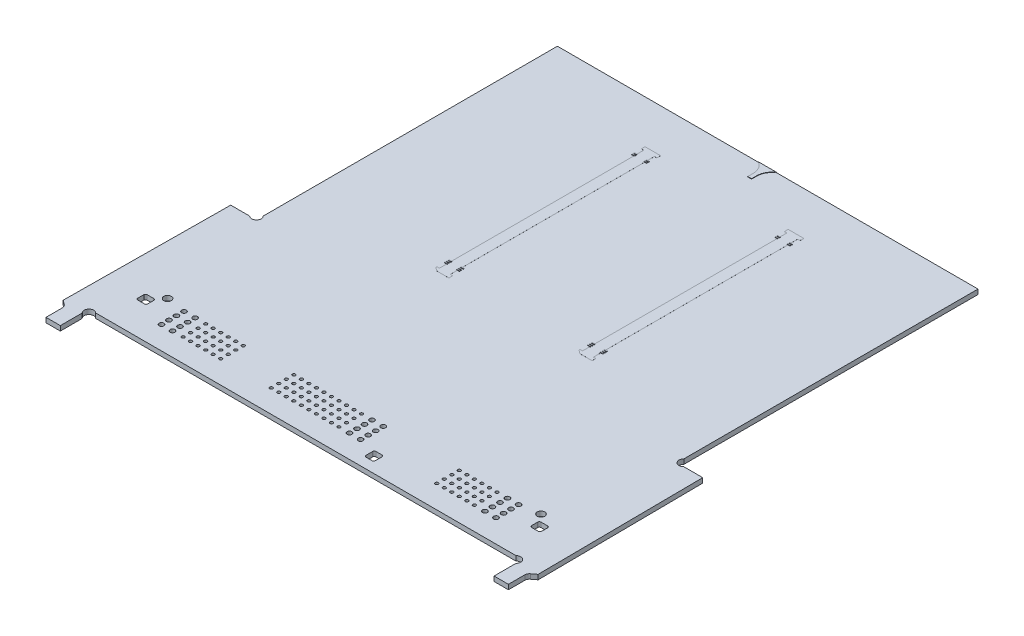
SolidWorks part; units mm, degrees
ref_plane "Front Plane" through (0, 0, 0) normal (0, 0, 1) x (1, 0, 0)
ref_plane "Top Plane" through (0, 0, 0) normal (0, 1, 0) x (1, 0, 0)
ref_plane "Right Plane" through (0, 0, 0) normal (1, 0, 0) x (0, 0, -1)
sketch "Sketch3" plane through (0, 0, 0) normal (0, 1, 0) x (1, 0, 0)
  line L0 (25.59, 116.4045) -> (25.59, 48.5345)
  line L1 (25.59, 116.4045) -> (25.59, 48.5345)
  line L2 (0, -0.0549) -> (0.0658, -0.0549)
  line L3 (-63.796, -10.1915) -> (-63.796, -8.1915)
  line L4 (-64.35, -7.6375) -> (-66.55, -7.6375)
  line L5 (-67.104, -8.1915) -> (-67.104, -10.1915)
  line L6 (-66.55, -10.7455) -> (-64.35, -10.7455)
  line L7 (66.55, -7.6375) -> (64.35, -7.6375)
  line L8 (63.796, -8.1915) -> (63.796, -10.1915)
  line L9 (64.35, -10.7455) -> (66.55, -10.7455)
  line L10 (67.104, -10.1915) -> (67.104, -8.1915)
  line L11 (16.6, -18.0455) -> (18.6, -18.0455)
  line L12 (19.154, -17.4915) -> (19.154, -15.2915)
  line L13 (18.6, -14.7375) -> (16.6, -14.7375)
  line L14 (16.046, -15.2915) -> (16.046, -17.4915)
  line L15 (69.8881, 132.0459) -> (2.9755, 132.0459)
  line L16 (69.8881, 34.2692) -> (69.8881, 132.0459)
  line L17 (78.4293, 32.0241) -> (72.1332, 32.0241)
  line L18 (78.9108, -23.1525) -> (78.4293, 32.0241)
  line L19 (77.4584, -24.2627) -> (78.9108, -23.1525)
  line L20 (76.835, -30.9607) -> (76.835, -25.5239)
  line L21 (72.0705, -30.9607) -> (76.835, -30.9607)
  line L22 (72.0705, -23.6916) -> (72.0705, -30.9607)
  line L23 (-69.8254, -21.4465) -> (69.8254, -21.4465)
  line L24 (-72.0705, -30.9607) -> (-72.0705, -23.6916)
  line L25 (-76.835, -30.9607) -> (-72.0705, -30.9607)
  line L26 (-76.835, -25.5239) -> (-76.835, -30.9607)
  line L27 (-78.9108, -23.1525) -> (-77.4584, -24.2627)
  line L28 (-78.4293, 32.0241) -> (-78.9108, -23.1525)
  line L29 (-72.1332, 32.0241) -> (-78.4293, 32.0241)
  line L30 (-69.8881, 132.0459) -> (-69.8881, 34.2692)
  line L31 (-2.9755, 132.0459) -> (-69.8881, 132.0459)
  line L32 (-0.635, 127.7677) -> (-0.635, 126.0497)
  line L33 (-0.635, 126.0497) -> (0.635, 126.0497)
  line L34 (0.635, 126.0497) -> (0.635, 127.7677)
  line L35 (-2.9755, 132.0459) -> (2.9755, 132.0459)
  line L36 (24.55, 47.2845) -> (26.4, 47.2845)
  line L37 (24.55, 47.2845) -> (26.4, 47.2845)
  line L38 (22.4, 47.2845) -> (21.2, 48.1248)
  line L39 (22.4, 47.2845) -> (21.2, 48.1248)
  line L40 (22.01, 48.5345) -> (22.01, 116.4045)
  line L41 (22.01, 48.5345) -> (22.01, 116.4045)
  line L42 (21.2, 48.5345) -> (22.01, 48.5345)
  line L43 (21.2, 48.5345) -> (22.01, 48.5345)
  line L44 (25.59, 48.5345) -> (26.4, 48.5345)
  line L45 (25.59, 48.5345) -> (26.4, 48.5345)
  line L46 (21.2, 48.1248) -> (21.2, 48.5345)
  line L47 (21.2, 48.1248) -> (21.2, 48.5345)
  line L48 (26.4, 47.2845) -> (26.4, 48.5345)
  line L49 (26.4, 47.2845) -> (26.4, 48.5345)
  line L50 (26.4, 116.4045) -> (25.59, 116.4045)
  line L51 (26.4, 116.4045) -> (25.59, 116.4045)
  line L52 (26.4, 116.4045) -> (26.4, 117.6545)
  line L53 (26.4, 116.4045) -> (26.4, 117.6545)
  line L54 (26.4, 117.6545) -> (24.55, 117.6545)
  line L55 (26.4, 117.6545) -> (24.55, 117.6545)
  line L56 (21.2, 116.4045) -> (21.2, 117.6545)
  line L57 (21.2, 116.4045) -> (21.2, 117.6545)
  line L58 (22.01, 116.4045) -> (21.2, 116.4045)
  line L59 (22.01, 116.4045) -> (21.2, 116.4045)
  line L60 (-25.59, 48.5497) -> (-25.59, 116.4197)
  line L61 (-25.59, 48.5497) -> (-25.59, 116.4197)
  line L62 (-25.2, 47.2997) -> (-26.4, 48.1399)
  line L63 (-25.2, 47.2997) -> (-26.4, 48.1399)
  line L64 (-25.2, 47.2997) -> (-24.55, 47.2997)
  line L65 (-25.2, 47.2997) -> (-24.55, 47.2997)
  line L66 (-26.4, 48.1399) -> (-26.4, 48.5497)
  line L67 (-26.4, 48.1399) -> (-26.4, 48.5497)
  line L68 (-25.59, 116.4197) -> (-26.4, 116.4197)
  line L69 (-25.59, 116.4197) -> (-26.4, 116.4197)
  line L70 (-26.4, 116.4197) -> (-26.4, 117.6697)
  line L71 (-26.4, 116.4197) -> (-26.4, 117.6697)
  line L72 (-24.55, 117.6697) -> (-26.4, 117.6697)
  line L73 (-24.55, 117.6697) -> (-26.4, 117.6697)
  line L74 (-21.2, 117.6697) -> (-23.05, 117.6697)
  line L75 (-21.2, 117.6697) -> (-23.05, 117.6697)
  line L76 (-21.2, 116.4197) -> (-21.2, 117.6697)
  line L77 (-21.2, 116.4197) -> (-21.2, 117.6697)
  line L78 (-22.01, 116.4197) -> (-22.01, 48.5497)
  line L79 (-22.01, 116.4197) -> (-22.01, 48.5497)
  line L80 (-21.2, 116.4197) -> (-22.01, 116.4197)
  line L81 (-21.2, 116.4197) -> (-22.01, 116.4197)
  line L82 (-21.2, 47.2997) -> (-21.2, 48.5497)
  line L83 (-21.2, 47.2997) -> (-21.2, 48.5497)
  line L84 (-22.01, 48.5497) -> (-21.2, 48.5497)
  line L85 (-22.01, 48.5497) -> (-21.2, 48.5497)
  line L86 (-26.4, 48.5497) -> (-25.59, 48.5497)
  line L87 (-26.4, 48.5497) -> (-25.59, 48.5497)
  line L96 (-25.38, 51.1872) -> (-26.3, 51.1872)
  line L97 (-25.38, 50.9172) -> (-25.38, 51.1872)
  line L98 (-26.3, 50.9172) -> (-25.38, 50.9172)
  line L99 (-26.3, 51.1872) -> (-26.3, 50.9172)
  line L100 (-25.38, 51.1872) -> (-26.3, 51.1872)
  line L101 (-25.38, 50.9172) -> (-25.38, 51.1872)
  line L102 (-26.3, 50.9172) -> (-25.38, 50.9172)
  line L103 (-26.3, 51.1872) -> (-26.3, 50.9172)
  line L104 (-25.38, 51.8222) -> (-26.3, 51.8222)
  line L105 (-25.38, 51.5522) -> (-25.38, 51.8222)
  line L106 (-26.3, 51.5522) -> (-25.38, 51.5522)
  line L107 (-26.3, 51.8222) -> (-26.3, 51.5522)
  line L108 (-25.38, 51.8222) -> (-26.3, 51.8222)
  line L109 (-25.38, 51.5522) -> (-25.38, 51.8222)
  line L110 (-26.3, 51.5522) -> (-25.38, 51.5522)
  line L111 (-26.3, 51.8222) -> (-26.3, 51.5522)
  line L112 (-25.38, 52.4572) -> (-26.3, 52.4572)
  line L113 (-25.38, 52.1872) -> (-25.38, 52.4572)
  line L114 (-26.3, 52.1872) -> (-25.38, 52.1872)
  line L115 (-26.3, 52.4572) -> (-26.3, 52.1872)
  line L116 (-25.38, 52.4572) -> (-26.3, 52.4572)
  line L117 (-25.38, 52.1872) -> (-25.38, 52.4572)
  line L118 (-26.3, 52.1872) -> (-25.38, 52.1872)
  line L119 (-26.3, 52.4572) -> (-26.3, 52.1872)
  line L120 (-21.3, 51.1872) -> (-22.22, 51.1872)
  line L121 (-21.3, 50.9172) -> (-21.3, 51.1872)
  line L122 (-22.22, 50.9172) -> (-21.3, 50.9172)
  line L123 (-22.22, 51.1872) -> (-22.22, 50.9172)
  line L124 (-21.3, 51.1872) -> (-22.22, 51.1872)
  line L125 (-21.3, 50.9172) -> (-21.3, 51.1872)
  line L126 (-22.22, 50.9172) -> (-21.3, 50.9172)
  line L127 (-22.22, 51.1872) -> (-22.22, 50.9172)
  line L128 (-21.3, 51.8222) -> (-22.22, 51.8222)
  line L129 (-21.3, 51.5522) -> (-21.3, 51.8222)
  line L130 (-22.22, 51.5522) -> (-21.3, 51.5522)
  line L131 (-22.22, 51.8222) -> (-22.22, 51.5522)
  line L132 (-21.3, 51.8222) -> (-22.22, 51.8222)
  line L133 (-21.3, 51.5522) -> (-21.3, 51.8222)
  line L134 (-22.22, 51.5522) -> (-21.3, 51.5522)
  line L135 (-22.22, 51.8222) -> (-22.22, 51.5522)
  line L136 (-21.3, 52.4572) -> (-22.22, 52.4572)
  line L137 (-21.3, 52.1872) -> (-21.3, 52.4572)
  line L138 (-22.22, 52.1872) -> (-21.3, 52.1872)
  line L139 (-22.22, 52.4572) -> (-22.22, 52.1872)
  line L140 (-21.3, 52.4572) -> (-22.22, 52.4572)
  line L141 (-21.3, 52.1872) -> (-21.3, 52.4572)
  line L142 (-22.22, 52.1872) -> (-21.3, 52.1872)
  line L143 (-22.22, 52.4572) -> (-22.22, 52.1872)
  line L144 (-25.38, 113.4172) -> (-26.3, 113.4172)
  line L145 (-25.38, 113.1472) -> (-25.38, 113.4172)
  line L146 (-26.3, 113.1472) -> (-25.38, 113.1472)
  line L147 (-26.3, 113.4172) -> (-26.3, 113.1472)
  line L148 (-25.38, 113.4172) -> (-26.3, 113.4172)
  line L149 (-25.38, 113.1472) -> (-25.38, 113.4172)
  line L150 (-26.3, 113.1472) -> (-25.38, 113.1472)
  line L151 (-26.3, 113.4172) -> (-26.3, 113.1472)
  line L152 (-25.38, 114.0522) -> (-26.3, 114.0522)
  line L153 (-25.38, 113.7822) -> (-25.38, 114.0522)
  line L154 (-26.3, 113.7822) -> (-25.38, 113.7822)
  line L155 (-26.3, 114.0522) -> (-26.3, 113.7822)
  line L156 (-25.38, 114.0522) -> (-26.3, 114.0522)
  line L157 (-25.38, 113.7822) -> (-25.38, 114.0522)
  line L158 (-26.3, 113.7822) -> (-25.38, 113.7822)
  line L159 (-26.3, 114.0522) -> (-26.3, 113.7822)
  line L160 (-21.3, 113.4172) -> (-22.22, 113.4172)
  line L161 (-21.3, 113.1472) -> (-21.3, 113.4172)
  line L162 (-22.22, 113.1472) -> (-21.3, 113.1472)
  line L163 (-22.22, 113.4172) -> (-22.22, 113.1472)
  line L164 (-21.3, 113.4172) -> (-22.22, 113.4172)
  line L165 (-21.3, 113.1472) -> (-21.3, 113.4172)
  line L166 (-22.22, 113.1472) -> (-21.3, 113.1472)
  line L167 (-22.22, 113.4172) -> (-22.22, 113.1472)
  line L168 (-21.3, 114.0522) -> (-22.22, 114.0522)
  line L169 (-21.3, 113.7822) -> (-21.3, 114.0522)
  line L170 (-22.22, 113.7822) -> (-21.3, 113.7822)
  line L171 (-22.22, 114.0522) -> (-22.22, 113.7822)
  line L172 (-21.3, 114.0522) -> (-22.22, 114.0522)
  line L173 (-21.3, 113.7822) -> (-21.3, 114.0522)
  line L174 (-22.22, 113.7822) -> (-21.3, 113.7822)
  line L175 (-22.22, 114.0522) -> (-22.22, 113.7822)
  line L176 (26.3, 114.0522) -> (25.38, 114.0522)
  line L177 (26.3, 113.7822) -> (26.3, 114.0522)
  line L178 (25.38, 113.7822) -> (26.3, 113.7822)
  line L179 (25.38, 114.0522) -> (25.38, 113.7822)
  line L180 (26.3, 114.0522) -> (25.38, 114.0522)
  line L181 (26.3, 113.7822) -> (26.3, 114.0522)
  line L182 (25.38, 113.7822) -> (26.3, 113.7822)
  line L183 (25.38, 114.0522) -> (25.38, 113.7822)
  line L184 (26.3, 113.4172) -> (25.38, 113.4172)
  line L185 (26.3, 113.1472) -> (26.3, 113.4172)
  line L186 (25.38, 113.1472) -> (26.3, 113.1472)
  line L187 (25.38, 113.4172) -> (25.38, 113.1472)
  line L188 (26.3, 113.4172) -> (25.38, 113.4172)
  line L189 (26.3, 113.1472) -> (26.3, 113.4172)
  line L190 (25.38, 113.1472) -> (26.3, 113.1472)
  line L191 (25.38, 113.4172) -> (25.38, 113.1472)
  line L192 (22.22, 113.4172) -> (21.3, 113.4172)
  line L193 (22.22, 113.1472) -> (22.22, 113.4172)
  line L194 (21.3, 113.1472) -> (22.22, 113.1472)
  line L195 (21.3, 113.4172) -> (21.3, 113.1472)
  line L196 (22.22, 113.4172) -> (21.3, 113.4172)
  line L197 (22.22, 113.1472) -> (22.22, 113.4172)
  line L198 (21.3, 113.1472) -> (22.22, 113.1472)
  line L199 (21.3, 113.4172) -> (21.3, 113.1472)
  line L200 (22.22, 114.0522) -> (21.3, 114.0522)
  line L201 (22.22, 113.7822) -> (22.22, 114.0522)
  line L202 (21.3, 113.7822) -> (22.22, 113.7822)
  line L203 (21.3, 114.0522) -> (21.3, 113.7822)
  line L204 (22.22, 114.0522) -> (21.3, 114.0522)
  line L205 (22.22, 113.7822) -> (22.22, 114.0522)
  line L206 (21.3, 113.7822) -> (22.22, 113.7822)
  line L207 (21.3, 114.0522) -> (21.3, 113.7822)
  line L208 (22.22, 51.1872) -> (21.3, 51.1872)
  line L209 (22.22, 50.9172) -> (22.22, 51.1872)
  line L210 (21.3, 50.9172) -> (22.22, 50.9172)
  line L211 (21.3, 51.1872) -> (21.3, 50.9172)
  line L212 (22.22, 51.1872) -> (21.3, 51.1872)
  line L213 (22.22, 50.9172) -> (22.22, 51.1872)
  line L214 (21.3, 50.9172) -> (22.22, 50.9172)
  line L215 (21.3, 51.1872) -> (21.3, 50.9172)
  line L216 (22.22, 51.8222) -> (21.3, 51.8222)
  line L217 (22.22, 51.5522) -> (22.22, 51.8222)
  line L218 (21.3, 51.5522) -> (22.22, 51.5522)
  line L219 (21.3, 51.8222) -> (21.3, 51.5522)
  line L220 (22.22, 51.8222) -> (21.3, 51.8222)
  line L221 (22.22, 51.5522) -> (22.22, 51.8222)
  line L222 (21.3, 51.5522) -> (22.22, 51.5522)
  line L223 (21.3, 51.8222) -> (21.3, 51.5522)
  line L224 (22.22, 52.4572) -> (21.3, 52.4572)
  line L225 (22.22, 52.1872) -> (22.22, 52.4572)
  line L226 (21.3, 52.1872) -> (22.22, 52.1872)
  line L227 (21.3, 52.4572) -> (21.3, 52.1872)
  line L228 (22.22, 52.4572) -> (21.3, 52.4572)
  line L229 (22.22, 52.1872) -> (22.22, 52.4572)
  line L230 (21.3, 52.1872) -> (22.22, 52.1872)
  line L231 (21.3, 52.4572) -> (21.3, 52.1872)
  line L232 (26.3, 51.1872) -> (25.38, 51.1872)
  line L233 (26.3, 50.9172) -> (26.3, 51.1872)
  line L234 (25.38, 50.9172) -> (26.3, 50.9172)
  line L235 (25.38, 51.1872) -> (25.38, 50.9172)
  line L236 (26.3, 51.1872) -> (25.38, 51.1872)
  line L237 (26.3, 50.9172) -> (26.3, 51.1872)
  line L238 (25.38, 50.9172) -> (26.3, 50.9172)
  line L239 (25.38, 51.1872) -> (25.38, 50.9172)
  line L240 (26.3, 51.8222) -> (25.38, 51.8222)
  line L241 (26.3, 51.5522) -> (26.3, 51.8222)
  line L242 (25.38, 51.5522) -> (26.3, 51.5522)
  line L243 (25.38, 51.8222) -> (25.38, 51.5522)
  line L244 (26.3, 51.8222) -> (25.38, 51.8222)
  line L245 (26.3, 51.5522) -> (26.3, 51.8222)
  line L246 (25.38, 51.5522) -> (26.3, 51.5522)
  line L247 (25.38, 51.8222) -> (25.38, 51.5522)
  line L248 (26.3, 52.4572) -> (25.38, 52.4572)
  line L249 (26.3, 52.1872) -> (26.3, 52.4572)
  line L250 (25.38, 52.1872) -> (26.3, 52.1872)
  line L251 (25.38, 52.4572) -> (25.38, 52.1872)
  line L252 (26.3, 52.4572) -> (25.38, 52.4572)
  line L253 (26.3, 52.1872) -> (26.3, 52.4572)
  line L254 (25.38, 52.1872) -> (26.3, 52.1872)
  line L255 (25.38, 52.4572) -> (25.38, 52.1872)
  line L260 (24.8, 117.6697) -> (26.4, 117.6697) construction
  line L261 (26.4, 116.4197) -> (26.4, 117.6697) construction
  line L262 (25.59, 116.4197) -> (26.4, 116.4197) construction
  line L263 (21.2, 117.6697) -> (21.2, 116.4197) construction
  line L264 (21.2, 116.4197) -> (22.01, 116.4197) construction
  line L265 (22.01, 49.7997) -> (22.01, 48.5497) construction
  line L266 (25.59, 48.5497) -> (25.59, 49.7997) construction
  line L267 (26.4, 48.5497) -> (25.59, 48.5497) construction
  line L268 (21.2, 48.5497) -> (21.2, 48.1399) construction
  line L269 (22.01, 48.5497) -> (21.2, 48.5497) construction
  line L270 (26.4, 47.2997) -> (26.4, 48.5497) construction
  line L271 (22.4, 47.2997) -> (22.8, 47.2997) construction
  line L272 (21.2, 48.1399) -> (22.4, 47.2997) construction
  line L273 (24.8, 117.6697) -> (26.4, 117.6697)
  line L274 (26.4, 116.4197) -> (26.4, 117.6697)
  line L275 (25.59, 116.4197) -> (26.4, 116.4197)
  line L276 (21.2, 117.6697) -> (21.2, 116.4197)
  line L277 (21.2, 116.4197) -> (22.01, 116.4197)
  line L278 (22.01, 49.7997) -> (22.01, 48.5497)
  line L279 (25.59, 48.5497) -> (25.59, 49.7997)
  line L280 (26.4, 48.5497) -> (25.59, 48.5497)
  line L281 (21.2, 48.5497) -> (21.2, 48.1399)
  line L282 (22.01, 48.5497) -> (21.2, 48.5497)
  line L283 (26.4, 47.2997) -> (26.4, 48.5497)
  line L284 (22.4, 47.2997) -> (22.8, 47.2997)
  line L285 (21.2, 48.1399) -> (22.4, 47.2997)
  arc A0 (-64.35, -10.7455) -> (-63.796, -10.1915) centre (-64.35, -10.1915) ccw
  arc A1 (-63.796, -8.1915) -> (-64.35, -7.6375) centre (-64.35, -8.1915) ccw
  arc A2 (-66.55, -7.6375) -> (-67.104, -8.1915) centre (-66.55, -8.1915) ccw
  arc A3 (-67.104, -10.1915) -> (-66.55, -10.7455) centre (-66.55, -10.1915) ccw
  circle A4 centre (-48.4, -6.339) radius 0.508
  circle A5 centre (-55.6, -6.339) radius 0.7937
  circle A6 centre (10.6, -6.339) radius 0.7937
  circle A7 centre (55.6, -6.339) radius 0.7938
  circle A8 centre (6.9, -6.339) radius 0.7938
  circle A9 centre (3.4, -6.339) radius 0.508
  circle A10 centre (51.9, -6.339) radius 0.7938
  circle A11 centre (10.6, -8.839) radius 0.7938
  circle A12 centre (55.6, -8.839) radius 0.7937
  circle A13 centre (6.9, -8.839) radius 0.7938
  circle A14 centre (51.9, -8.839) radius 0.7938
  circle A15 centre (-51.9, -6.339) radius 0.7938
  circle A16 centre (-55.6, -8.839) radius 0.7937
  circle A17 centre (-51.9, -8.839) radius 0.7938
  circle A18 centre (-55.6, -11.339) radius 0.7938
  circle A19 centre (-51.9, -11.339) radius 0.7937
  circle A20 centre (-55.6, -13.839) radius 0.7938
  circle A21 centre (-51.9, -13.839) radius 0.7937
  circle A22 centre (10.6, -11.339) radius 0.7938
  circle A23 centre (55.6, -11.339) radius 0.7937
  circle A24 centre (6.9, -11.339) radius 0.7938
  circle A25 centre (51.9, -11.339) radius 0.7938
  circle A26 centre (10.6, -13.839) radius 0.7938
  circle A27 centre (55.6, -13.839) radius 0.7937
  circle A28 centre (48.4, -6.339) radius 0.508
  circle A29 centre (6.9, -13.839) radius 0.7938
  circle A30 centre (-45.9, -6.339) radius 0.508
  circle A31 centre (-43.4, -6.339) radius 0.508
  circle A32 centre (-40.9, -6.339) radius 0.508
  circle A33 centre (-38.4, -6.339) radius 0.508
  circle A34 centre (-35.9, -6.339) radius 0.508
  circle A35 centre (-48.4, -8.839) radius 0.508
  circle A36 centre (-45.9, -8.839) radius 0.508
  circle A37 centre (-43.4, -8.839) radius 0.508
  circle A38 centre (-40.9, -8.839) radius 0.508
  circle A39 centre (-38.4, -8.839) radius 0.508
  circle A40 centre (-35.9, -8.839) radius 0.508
  circle A41 centre (-48.4, -11.339) radius 0.508
  circle A42 centre (-45.9, -11.339) radius 0.508
  circle A43 centre (-43.4, -11.339) radius 0.508
  circle A44 centre (-40.9, -11.339) radius 0.508
  circle A45 centre (-38.4, -11.339) radius 0.508
  circle A46 centre (-35.9, -11.339) radius 0.508
  circle A47 centre (-48.4, -13.839) radius 0.508
  circle A48 centre (-45.9, -13.839) radius 0.508
  circle A49 centre (-43.4, -13.839) radius 0.508
  circle A50 centre (-40.9, -13.839) radius 0.508
  circle A51 centre (-38.4, -13.839) radius 0.508
  circle A52 centre (-35.9, -13.839) radius 0.508
  circle A53 centre (51.9, -13.839) radius 0.7938
  circle A54 centre (45.9, -6.339) radius 0.508
  circle A55 centre (43.4, -6.339) radius 0.508
  circle A56 centre (40.9, -6.339) radius 0.508
  circle A57 centre (38.4, -6.339) radius 0.508
  circle A58 centre (35.9, -6.339) radius 0.508
  circle A59 centre (48.4, -8.839) radius 0.508
  circle A60 centre (45.9, -8.839) radius 0.508
  circle A61 centre (43.4, -8.839) radius 0.508
  circle A62 centre (40.9, -8.839) radius 0.508
  circle A63 centre (38.4, -8.839) radius 0.508
  circle A64 centre (35.9, -8.839) radius 0.508
  circle A65 centre (48.4, -11.339) radius 0.508
  circle A66 centre (45.9, -11.339) radius 0.508
  circle A67 centre (43.4, -11.339) radius 0.508
  circle A68 centre (40.9, -11.339) radius 0.508
  circle A69 centre (38.4, -11.339) radius 0.508
  circle A70 centre (35.9, -11.339) radius 0.508
  circle A71 centre (48.4, -13.839) radius 0.508
  circle A72 centre (45.9, -13.839) radius 0.508
  circle A73 centre (43.4, -13.839) radius 0.508
  circle A74 centre (40.9, -13.839) radius 0.508
  circle A75 centre (38.4, -13.839) radius 0.508
  circle A76 centre (35.9, -13.839) radius 0.508
  circle A77 centre (0.9, -6.339) radius 0.508
  circle A78 centre (-1.6, -6.339) radius 0.508
  circle A79 centre (-4.1, -6.339) radius 0.508
  circle A80 centre (-6.6, -6.339) radius 0.508
  circle A81 centre (-9.1, -6.339) radius 0.508
  circle A82 centre (-11.6, -6.339) radius 0.508
  circle A83 centre (-14.1, -6.339) radius 0.508
  circle A84 centre (-16.6, -6.339) radius 0.508
  circle A85 centre (-19.1, -6.339) radius 0.508
  circle A86 centre (3.4, -8.839) radius 0.508
  circle A87 centre (0.9, -8.839) radius 0.508
  circle A88 centre (-1.6, -8.839) radius 0.508
  circle A89 centre (-4.1, -8.839) radius 0.508
  circle A90 centre (-6.6, -8.839) radius 0.508
  circle A91 centre (-9.1, -8.839) radius 0.508
  circle A92 centre (-11.6, -8.839) radius 0.508
  circle A93 centre (-14.1, -8.839) radius 0.508
  circle A94 centre (-16.6, -8.839) radius 0.508
  circle A95 centre (-19.1, -8.839) radius 0.508
  circle A96 centre (3.4, -11.339) radius 0.508
  circle A97 centre (0.9, -11.339) radius 0.508
  circle A98 centre (-1.6, -11.339) radius 0.508
  circle A99 centre (-4.1, -11.339) radius 0.508
  circle A100 centre (-6.6, -11.339) radius 0.508
  circle A101 centre (-9.1, -11.339) radius 0.508
  circle A102 centre (-11.6, -11.339) radius 0.508
  circle A103 centre (-14.1, -11.339) radius 0.508
  circle A104 centre (-16.6, -11.339) radius 0.508
  circle A105 centre (-19.1, -11.339) radius 0.508
  circle A106 centre (3.4, -13.839) radius 0.508
  circle A107 centre (0.9, -13.839) radius 0.508
  circle A108 centre (-1.6, -13.839) radius 0.508
  circle A109 centre (-4.1, -13.839) radius 0.508
  circle A110 centre (-6.6, -13.839) radius 0.508
  circle A111 centre (-9.1, -13.839) radius 0.508
  circle A112 centre (-11.6, -13.839) radius 0.508
  circle A113 centre (-14.1, -13.839) radius 0.508
  circle A114 centre (-16.6, -13.839) radius 0.508
  circle A115 centre (-19.1, -13.839) radius 0.508
  circle A116 centre (-62.05, -5.3415) radius 1.254
  circle A117 centre (62.05, -5.3415) radius 1.254
  arc A118 (64.35, -7.6375) -> (63.796, -8.1915) centre (64.35, -8.1915) ccw
  arc A119 (63.796, -10.1915) -> (64.35, -10.7455) centre (64.35, -10.1915) ccw
  arc A120 (66.55, -10.7455) -> (67.104, -10.1915) centre (66.55, -10.1915) ccw
  arc A121 (67.104, -8.1915) -> (66.55, -7.6375) centre (66.55, -8.1915) ccw
  arc A122 (18.6, -18.0455) -> (19.154, -17.4915) centre (18.6, -17.4915) ccw
  arc A123 (19.154, -15.2915) -> (18.6, -14.7375) centre (18.6, -15.2915) ccw
  arc A124 (16.6, -14.7375) -> (16.046, -15.2915) centre (16.6, -15.2915) ccw
  arc A125 (16.046, -17.4915) -> (16.6, -18.0455) centre (16.6, -17.4915) ccw
  arc A126 (69.8881, 34.2692) -> (72.1332, 32.0241) centre (71.0106, 33.1467) ccw
  arc A127 (77.4584, -24.2627) -> (76.835, -25.5239) centre (78.4225, -25.5239) ccw
  arc A128 (72.0705, -23.6916) -> (69.8254, -21.4465) centre (70.948, -22.569) ccw
  arc A129 (-69.8254, -21.4465) -> (-72.0705, -23.6916) centre (-70.948, -22.569) ccw
  arc A130 (-76.835, -25.5239) -> (-77.4584, -24.2627) centre (-78.4225, -25.5239) ccw
  arc A131 (-72.1332, 32.0241) -> (-69.8881, 34.2692) centre (-71.0106, 33.1467) ccw
  arc A132 (-0.635, 127.7677) -> (-2.9755, 132.0459) centre (-5.7152, 127.7677) ccw
  arc A133 (2.9755, 132.0459) -> (0.635, 127.7677) centre (5.7152, 127.7677) ccw
  circle A134 centre (23.8, 115.1697) radius 0.3 construction
  circle A135 centre (23.8, 49.7997) radius 0.4 construction
  circle A136 centre (23.8, 115.1697) radius 0.3
  circle A137 centre (23.8, 49.7997) radius 0.4
  circle A138 centre (-23.8, 115.1697) radius 0.3 construction
  circle A139 centre (-23.8, 49.7997) radius 0.4 construction
  circle A140 centre (-23.8, 115.1697) radius 0.3
  circle A141 centre (-23.8, 49.7997) radius 0.4
  circle A142 centre (-55.6, -6.339) radius 0.6
  circle A143 centre (-55.6, -6.339) radius 0.889
  dimension "D22" = 1.2
  dimension "D23" = 1.778
  dimension "D2" = 0
  dimension "D3" = 0
  dimension "D4" = 0
  dimension "D5" = 0
  dimension "D6" = 0
  dimension "D7" = 0
  dimension "D8" = 0
  dimension "D9" = 0
  dimension "D10" = 0
  dimension "D11" = 0
  dimension "D12" = 0
  dimension "D13" = 0
  dimension "D14" = 0
  dimension "D15" = 0
  dimension "D16" = 0
  dimension "D17" = 0
  dimension "D18" = 0
  dimension "D19" = 0
  dimension "D20" = 0
  dimension "D21" = 0
ref_plane "Plane1" [suppressed] through (0, 6.3807, 0.0557) normal (0, 1, 0.0087) x (-1, 0, 0)
sketch "Sketch1" [suppressed] plane through (0, 6.3807, 0.0557) normal (0, 1, 0.0087) x (-1, 0, 0)
  line L0 (-66.1, 7.8366) -> (-66.1, 9.1366) construction
  line L1 (-70.1421, -132.3548) -> (70.1421, -132.3548) construction
  line L2 (-70.1421, -132.3548) -> (-70.1421, -32.333) construction
  line L3 (-71.8165, 21.6456) -> (71.8165, 21.6456) construction
  line L4 (70.1421, -132.3548) -> (70.1421, -32.333) construction
  line L5 (-64.05, 8.1366) -> (-64.05, 10.1366) construction
  line L6 (-64.35, 7.8366) -> (-65.65, 7.8366) construction
  line L7 (-64.35, 10.4366) -> (-65.65, 10.4366) construction
  line L8 (-70.1421, -32.333) -> (-78.6811, -32.333) construction
  line L9 (77.089, 24.8099) -> (77.089, 31.1599) construction
  line L10 (-78.6811, -32.333) -> (-79.1659, 23.2224) construction
  line L11 (64.05, 8.1366) -> (64.05, 10.1366) construction
  line L12 (64.35, 10.4366) -> (65.65, 10.4366) construction
  line L13 (65.65, 10.4366) -> (66.55, 10.4366) construction
  line L14 (66.85, 8.1366) -> (66.85, 10.1366) construction
  line L15 (66.55, 7.8366) -> (65.65, 7.8366) construction
  line L16 (-68.15, 8.1366) -> (-68.15, 10.1366) construction
  line L17 (-66.85, 8.1366) -> (-66.85, 10.4366) construction
  line L18 (-65.65, 10.4366) -> (-66.0792, 10.4366) construction
  line L19 (-65.35, 10.1366) -> (-65.35, 8.1366) construction
  line L20 (0, -132.3548) -> (0, 0) construction
  line L21 (70.1421, -32.333) -> (78.6811, -32.333) construction
  line L22 (78.6811, -32.333) -> (79.1659, 23.2224) construction
  line L23 (-65.35, 9.1366) -> (-66.1, 9.1366) construction
  line L24 (64.35, 7.8366) -> (65.65, 7.8366) construction
  line L25 (-18.9, 16.1366) -> (-18.9, 15.7074) construction
  line L26 (-18.6, 16.4366) -> (-16.6, 16.4366) construction
  line L27 (-16.3, 15.7074) -> (-16.3, 16.1366) construction
  line L28 (-16.6, 13.6366) -> (-18.6, 13.6366) construction
  line L29 (-18.6, 14.9366) -> (-16.6, 14.9366) construction
  line L30 (-18.9, 16.1366) -> (-18.9, 15.2366) construction
  line L31 (-18.6, 16.4366) -> (-16.6, 16.4366) construction
  line L32 (-16.3, 15.2366) -> (-16.3, 16.1366) construction
  line L33 (-16.6, 13.6366) -> (-18.6, 13.6366) construction
  line L34 (-18.6, 14.9366) -> (-16.6, 14.9366) construction
  line L35 (-18.9, 15.6866) -> (-16.3, 15.6866) construction
  line L36 (71.8165, 21.6456) -> (71.8165, 31.1599) construction
  line L37 (77.089, 31.1599) -> (71.8165, 31.1599) construction
  line L38 (-77.089, 24.8099) -> (-77.089, 31.1599) construction
  line L39 (-77.089, 31.1599) -> (-71.8165, 31.1599) construction
  line L40 (-16.6, 17.7366) -> (-18.6, 17.7366) construction
  line L41 (-71.8165, 21.6456) -> (-71.8165, 31.1599) construction
  line L42 (-16.3, 16.1366) -> (-16.3, 17.4366) construction
  line L43 (-79.1659, 23.2224) -> (-77.089, 24.8099) construction
  line L44 (79.1659, 23.2224) -> (77.089, 24.8099) construction
  line L45 (-18.9, 16.1366) -> (-18.9, 17.4366) construction
  line L46 (-68.15, 8.1366) -> (-68.15, 10.1366) construction
  line L47 (-66.85, 8.1366) -> (-66.85, 10.1366) construction
  line L48 (-65.65, 10.4366) -> (-66.55, 10.4366) construction
  line L49 (-65.35, 10.1366) -> (-65.35, 8.1366) construction
  line L50 (-66.0792, 7.8366) -> (-65.65, 7.8366) construction
  line L51 (-66.55, 7.8366) -> (-65.65, 7.8366) construction
  line L52 (55.725, 6.1591) -> (55.475, 6.4091) construction
  line L53 (48.525, 6.1591) -> (48.275, 6.4091) construction
  line L54 (52.025, 6.1591) -> (51.775, 6.4091) construction
  line L55 (-6.9, 6.2841) -> (-3.4, 6.2841) construction
  line L56 (55.475, 6.4091) -> (55.475, 6.1591)
  line L57 (55.725, 6.4091) -> (55.475, 6.4091)
  line L58 (55.725, 6.1591) -> (55.725, 6.4091)
  line L59 (55.475, 6.1591) -> (55.725, 6.1591)
  line L60 (55.475, 6.4091) -> (55.475, 6.1591) construction
  line L61 (55.725, 6.4091) -> (55.475, 6.4091) construction
  line L62 (55.725, 6.1591) -> (55.725, 6.4091) construction
  line L63 (55.475, 6.1591) -> (55.725, 6.1591) construction
  line L64 (55.475, 8.9091) -> (55.475, 8.6591)
  line L65 (55.725, 8.9091) -> (55.475, 8.9091)
  line L66 (55.725, 8.6591) -> (55.725, 8.9091)
  line L67 (55.475, 8.6591) -> (55.725, 8.6591)
  line L68 (55.475, 8.9091) -> (55.475, 8.6591) construction
  line L69 (55.725, 8.9091) -> (55.475, 8.9091) construction
  line L70 (55.725, 8.6591) -> (55.725, 8.9091) construction
  line L71 (55.475, 8.6591) -> (55.725, 8.6591) construction
  line L72 (51.775, 6.4091) -> (51.775, 6.1591)
  line L73 (52.025, 6.4091) -> (51.775, 6.4091)
  line L74 (52.025, 6.1591) -> (52.025, 6.4091)
  line L75 (51.775, 6.1591) -> (52.025, 6.1591)
  line L76 (51.775, 6.4091) -> (51.775, 6.1591) construction
  line L77 (52.025, 6.4091) -> (51.775, 6.4091) construction
  line L78 (52.025, 6.1591) -> (52.025, 6.4091) construction
  line L79 (51.775, 6.1591) -> (52.025, 6.1591) construction
  line L80 (18.975, 6.4091) -> (18.975, 6.1591)
  line L81 (19.225, 6.4091) -> (18.975, 6.4091)
  line L82 (19.225, 6.1591) -> (19.225, 6.4091)
  line L83 (18.975, 6.1591) -> (19.225, 6.1591)
  line L84 (18.975, 6.4091) -> (18.975, 6.1591) construction
  line L85 (19.225, 6.4091) -> (18.975, 6.4091) construction
  line L86 (19.225, 6.1591) -> (19.225, 6.4091) construction
  line L87 (18.975, 6.1591) -> (19.225, 6.1591) construction
  line L88 (35.775, 6.4091) -> (35.775, 6.1591)
  line L89 (36.025, 6.4091) -> (35.775, 6.4091)
  line L90 (36.025, 6.1591) -> (36.025, 6.4091)
  line L91 (35.775, 6.1591) -> (36.025, 6.1591)
  line L92 (35.775, 6.4091) -> (35.775, 6.1591) construction
  line L93 (36.025, 6.4091) -> (35.775, 6.4091) construction
  line L94 (36.025, 6.1591) -> (36.025, 6.4091) construction
  line L95 (35.775, 6.1591) -> (36.025, 6.1591) construction
  line L96 (-10.725, 6.4091) -> (-10.725, 6.1591)
  line L97 (-10.475, 6.4091) -> (-10.725, 6.4091)
  line L98 (-10.475, 6.1591) -> (-10.475, 6.4091)
  line L99 (-10.725, 6.1591) -> (-10.475, 6.1591)
  line L100 (-10.725, 6.4091) -> (-10.725, 6.1591) construction
  line L101 (-10.475, 6.4091) -> (-10.725, 6.4091) construction
  line L102 (-10.475, 6.1591) -> (-10.475, 6.4091) construction
  line L103 (-10.725, 6.1591) -> (-10.475, 6.1591) construction
  line L104 (-36.025, 6.4091) -> (-36.025, 6.1591)
  line L105 (-35.775, 6.4091) -> (-36.025, 6.4091)
  line L106 (-35.775, 6.1591) -> (-35.775, 6.4091)
  line L107 (-36.025, 6.1591) -> (-35.775, 6.1591)
  line L108 (-36.025, 6.4091) -> (-36.025, 6.1591) construction
  line L109 (-35.775, 6.4091) -> (-36.025, 6.4091) construction
  line L110 (-35.775, 6.1591) -> (-35.775, 6.4091) construction
  line L111 (-36.025, 6.1591) -> (-35.775, 6.1591) construction
  line L112 (-55.725, 6.4091) -> (-55.725, 6.1591)
  line L113 (-55.475, 6.4091) -> (-55.725, 6.4091)
  line L114 (-55.475, 6.1591) -> (-55.475, 6.4091)
  line L115 (-55.725, 6.1591) -> (-55.475, 6.1591)
  line L116 (-55.725, 6.4091) -> (-55.725, 6.1591) construction
  line L117 (-55.475, 6.4091) -> (-55.725, 6.4091) construction
  line L118 (-55.475, 6.1591) -> (-55.475, 6.4091) construction
  line L119 (-55.725, 6.1591) -> (-55.475, 6.1591) construction
  line L120 (55.725, 8.6591) -> (55.475, 8.9091) construction
  line L121 (55.6, 8.7841) -> (55.6, 6.2841) construction
  line L122 (19.225, 6.1591) -> (18.975, 6.4091) construction
  line L123 (55.6, 6.2841) -> (51.9, 6.2841) construction
  line L124 (-35.775, 6.1591) -> (-36.025, 6.4091) construction
  line L125 (55.6, 6.2841) -> (55.6, 8.7841) construction
  line L126 (-51.9, 6.2841) -> (-48.4, 6.2841) construction
  line L127 (48.4, 6.2841) -> (45.9, 6.2841) construction
  line L128 (48.4, 6.2841) -> (48.4, 8.7841) construction
  line L129 (46.025, 6.1591) -> (45.775, 6.4091) construction
  line L130 (-10.475, 6.1591) -> (-10.725, 6.4091) construction
  line L131 (-10.6, 6.2841) -> (-6.9, 6.2841) construction
  line L132 (48.275, 6.4091) -> (48.275, 6.1591)
  line L133 (48.525, 6.4091) -> (48.275, 6.4091)
  line L134 (48.525, 6.1591) -> (48.525, 6.4091)
  line L135 (48.275, 6.1591) -> (48.525, 6.1591)
  line L136 (48.275, 6.4091) -> (48.275, 6.1591) construction
  line L137 (48.525, 6.4091) -> (48.275, 6.4091) construction
  line L138 (48.525, 6.1591) -> (48.525, 6.4091) construction
  line L139 (48.275, 6.1591) -> (48.525, 6.1591) construction
  line L140 (45.775, 6.4091) -> (45.775, 6.1591)
  line L141 (46.025, 6.4091) -> (45.775, 6.4091)
  line L142 (46.025, 6.1591) -> (46.025, 6.4091)
  line L143 (45.775, 6.1591) -> (46.025, 6.1591)
  line L144 (45.775, 6.4091) -> (45.775, 6.1591) construction
  line L145 (46.025, 6.4091) -> (45.775, 6.4091) construction
  line L146 (46.025, 6.1591) -> (46.025, 6.4091) construction
  line L147 (45.775, 6.1591) -> (46.025, 6.1591) construction
  line L148 (-55.475, 6.1591) -> (-55.725, 6.4091) construction
  line L149 (-10.6, 6.2841) -> (-10.6, 8.7841) construction
  line L150 (51.9, 6.2841) -> (48.4, 6.2841) construction
  line L151 (-48.4, 6.2841) -> (-45.9, 6.2841) construction
  line L152 (-48.4, 6.2841) -> (-48.4, 8.7841) construction
  line L153 (-3.4, 6.2841) -> (-0.9, 6.2841) construction
  line L154 (-3.4, 6.2841) -> (-3.4, 8.7841) construction
  line L155 (69.8881, -132.1008) -> (69.8881, -34.3241)
  line L156 (72.1332, -32.079) -> (69.8881, -32.079) construction
  line L157 (78.4293, -32.079) -> (78.9108, 23.0977)
  line L158 (78.9108, 23.0977) -> (77.4584, 24.2078)
  line L159 (76.835, 25.469) -> (76.835, 30.9059)
  line L160 (76.835, 30.9059) -> (72.0705, 30.9059)
  line L161 (72.0705, 23.6367) -> (72.0705, 30.9059)
  line L162 (-69.8254, 21.3916) -> (69.8254, 21.3916)
  line L163 (-72.0705, 23.6367) -> (-72.0705, 30.9059)
  line L164 (-76.835, 30.9059) -> (-72.0705, 30.9059)
  line L165 (-76.835, 25.469) -> (-76.835, 30.9059)
  line L166 (-78.9108, 23.0977) -> (-77.4584, 24.2078)
  line L167 (-78.4293, -32.079) -> (-78.9108, 23.0977)
  line L168 (-72.1332, -32.079) -> (-78.4293, -32.079)
  line L169 (-69.8881, -132.1008) -> (-69.8881, -34.3241)
  line L170 (-69.8881, -132.1008) -> (69.8881, -132.1008)
  line L171 (69.8881, -32.079) -> (69.8881, -34.3241) construction
  line L172 (-69.8881, -132.1008) -> (-69.8881, -32.079) construction
  line L173 (-69.8881, -32.079) -> (-78.4293, -32.079) construction
  line L174 (72.1332, -32.079) -> (78.4293, -32.079)
  line L175 (69.8881, -32.079) -> (78.4293, -32.079) construction
  line L176 (-78.9108, 23.0977) -> (-76.835, 24.6843) construction
  line L177 (69.8881, -132.1008) -> (69.8881, -32.079) construction
  line L178 (-76.835, 24.6843) -> (-76.835, 30.9059) construction
  line L179 (-72.0705, 21.3916) -> (72.0705, 21.3916) construction
  line L180 (-72.0705, 21.3916) -> (-72.0705, 30.9059) construction
  line L181 (-69.8254, 21.3916) -> (-72.0705, 21.3916) construction
  line L182 (-72.0705, 21.3916) -> (-72.0705, 23.6367) construction
  line L183 (76.835, 24.6843) -> (76.835, 30.9059) construction
  line L184 (78.9108, 23.0977) -> (76.835, 24.6843) construction
  line L185 (72.0705, 21.3916) -> (72.0705, 30.9059) construction
  line L186 (-66.55, 10.4366) -> (-66.85, 10.4366) construction
  line L187 (-66.85, 10.4366) -> (-66.85, 10.1366) construction
  line L188 (-67.104, 8.1366) -> (-67.104, 10.1366)
  line L189 (-65.65, 10.6906) -> (-66.55, 10.6906)
  line L190 (-64.35, 10.6906) -> (-65.65, 10.6906)
  line L191 (-63.796, 8.1366) -> (-63.796, 10.1366)
  line L192 (-64.35, 7.5826) -> (-65.65, 7.5826)
  line L193 (-66.55, 7.5826) -> (-65.65, 7.5826)
  line L194 (-16.6, 17.9906) -> (-18.6, 17.9906)
  line L195 (-19.154, 16.1366) -> (-19.154, 17.4366)
  line L196 (-19.154, 16.1366) -> (-19.154, 15.2366)
  line L197 (-18.6, 14.6826) -> (-16.6, 14.6826)
  line L198 (-16.046, 15.2366) -> (-16.046, 16.1366)
  line L199 (-16.046, 16.1366) -> (-16.046, 17.4366)
  line L200 (66.85, 10.1366) -> (66.85, 10.4366) construction
  line L201 (66.85, 10.4366) -> (66.55, 10.4366) construction
  line L202 (65.65, 10.6906) -> (66.55, 10.6906)
  line L203 (67.104, 8.1366) -> (67.104, 10.1366)
  line L204 (66.55, 7.5826) -> (65.65, 7.5826)
  line L205 (64.35, 7.5826) -> (65.65, 7.5826)
  line L206 (63.796, 8.1366) -> (63.796, 10.1366)
  line L207 (64.35, 10.6906) -> (65.65, 10.6906)
  arc A0 (-64.05, 8.1366) -> (-64.35, 7.8366) centre (-64.35, 8.1366) cw construction
  circle A1 centre (-62.05, 5.2866) radius 1 construction
  arc A2 (-64.35, 10.4366) -> (-64.05, 10.1366) centre (-64.35, 10.1366) cw construction
  circle A3 centre (-62.05, 5.2866) radius 1 construction
  arc A4 (-67.85, 10.4366) -> (-68.15, 10.1366) centre (-67.85, 10.1366) ccw construction
  arc A5 (-68.15, 8.1366) -> (-67.85, 7.8366) centre (-67.85, 8.1366) ccw construction
  arc A6 (-66.85, 8.1366) -> (-66.55, 7.8366) centre (-66.55, 8.1366) ccw construction
  arc A7 (-65.35, 10.1366) -> (-65.65, 10.4366) centre (-65.65, 10.1366) ccw construction
  arc A8 (-67.85, 10.4366) -> (-68.15, 10.1366) centre (-67.85, 10.1366) ccw construction
  arc A9 (-68.15, 8.1366) -> (-67.85, 7.8366) centre (-67.85, 8.1366) ccw construction
  arc A10 (-66.85, 8.1366) -> (-66.55, 7.8366) centre (-66.55, 8.1366) ccw construction
  arc A11 (-65.35, 10.1366) -> (-65.65, 10.4366) centre (-65.65, 10.1366) ccw construction
  arc A12 (-65.65, 7.8366) -> (-65.35, 8.1366) centre (-65.65, 8.1366) ccw construction
  arc A13 (-65.65, 7.8366) -> (-65.35, 8.1366) centre (-65.65, 8.1366) ccw construction
  arc A14 (64.05, 8.1366) -> (64.35, 7.8366) centre (64.35, 8.1366) ccw construction
  arc A15 (64.35, 10.4366) -> (64.05, 10.1366) centre (64.35, 10.1366) ccw construction
  arc A16 (66.85, 8.1366) -> (66.55, 7.8366) centre (66.55, 8.1366) cw construction
  circle A17 centre (62.05, 5.2866) radius 1 construction
  arc A18 (-18.6, 16.4366) -> (-18.9, 16.1366) centre (-18.6, 16.1366) ccw construction
  arc A19 (-16.3, 16.1366) -> (-16.6, 16.4366) centre (-16.6, 16.1366) ccw construction
  arc A20 (-18.9, 13.9366) -> (-18.6, 13.6366) centre (-18.6, 13.9366) ccw construction
  arc A21 (-16.6, 13.6366) -> (-16.3, 13.9366) centre (-16.6, 13.9366) ccw construction
  arc A22 (-18.9, 15.2366) -> (-18.6, 14.9366) centre (-18.6, 15.2366) ccw construction
  arc A23 (-16.6, 14.9366) -> (-16.3, 15.2366) centre (-16.6, 15.2366) ccw construction
  arc A24 (-18.6, 16.4366) -> (-18.9, 16.1366) centre (-18.6, 16.1366) ccw construction
  arc A25 (-16.3, 16.1366) -> (-16.6, 16.4366) centre (-16.6, 16.1366) ccw construction
  arc A26 (-18.9, 13.9366) -> (-18.6, 13.6366) centre (-18.6, 13.9366) ccw construction
  arc A27 (-16.6, 13.6366) -> (-16.3, 13.9366) centre (-16.6, 13.9366) ccw construction
  arc A28 (-18.9, 15.2366) -> (-18.6, 14.9366) centre (-18.6, 15.2366) ccw construction
  arc A29 (-16.6, 14.9366) -> (-16.3, 15.2366) centre (-16.6, 15.2366) ccw construction
  arc A30 (-16.6, 17.7366) -> (-16.3, 17.4366) centre (-16.6, 17.4366) cw construction
  arc A31 (-18.9, 17.4366) -> (-18.6, 17.7366) centre (-18.6, 17.4366) cw construction
  circle A32 centre (55.6, 6.2841) radius 0.7937
  circle A33 centre (-10.6, 6.2841) radius 0.7938
  circle A34 centre (-55.6, 6.2841) radius 0.7938
  circle A35 centre (-6.9, 6.2841) radius 0.7938
  circle A36 centre (-51.9, 6.2841) radius 0.7938
  circle A37 centre (-10.6, 8.7841) radius 0.7938
  circle A38 centre (-55.6, 8.7841) radius 0.7938
  circle A39 centre (-6.9, 8.7841) radius 0.7938
  circle A40 centre (-51.9, 8.7841) radius 0.7938
  circle A41 centre (-10.6, 11.2841) radius 0.7938
  circle A42 centre (51.9, 6.2841) radius 0.7937
  circle A43 centre (55.6, 8.7841) radius 0.7937
  circle A44 centre (51.9, 8.7841) radius 0.7937
  circle A45 centre (55.6, 11.2841) radius 0.7937
  circle A46 centre (51.9, 11.2841) radius 0.7937
  circle A47 centre (55.6, 13.7841) radius 0.7937
  circle A48 centre (51.9, 13.7841) radius 0.7937
  circle A49 centre (-55.6, 11.2841) radius 0.7938
  circle A50 centre (-6.9, 11.2841) radius 0.7938
  circle A51 centre (-51.9, 11.2841) radius 0.7938
  circle A52 centre (-10.6, 13.7841) radius 0.7938
  circle A53 centre (-55.6, 13.7841) radius 0.7938
  circle A54 centre (-6.9, 13.7841) radius 0.7938
  circle A55 centre (-51.9, 13.7841) radius 0.7938
  circle A56 centre (48.4, 6.2841) radius 0.508
  circle A57 centre (-3.4, 6.2841) radius 0.508
  circle A58 centre (-48.4, 6.2841) radius 0.508
  circle A59 centre (45.9, 6.2841) radius 0.508
  circle A60 centre (43.4, 6.2841) radius 0.508
  circle A61 centre (40.9, 6.2841) radius 0.508
  circle A62 centre (38.4, 6.2841) radius 0.508
  circle A63 centre (35.9, 6.2841) radius 0.508
  circle A64 centre (48.4, 8.7841) radius 0.508
  circle A65 centre (45.9, 8.7841) radius 0.508
  circle A66 centre (43.4, 8.7841) radius 0.508
  circle A67 centre (40.9, 8.7841) radius 0.508
  circle A68 centre (38.4, 8.7841) radius 0.508
  circle A69 centre (35.9, 8.7841) radius 0.508
  circle A70 centre (48.4, 11.2841) radius 0.508
  circle A71 centre (45.9, 11.2841) radius 0.508
  circle A72 centre (43.4, 11.2841) radius 0.508
  circle A73 centre (40.9, 11.2841) radius 0.508
  circle A74 centre (38.4, 11.2841) radius 0.508
  circle A75 centre (35.9, 11.2841) radius 0.508
  circle A76 centre (48.4, 13.7841) radius 0.508
  circle A77 centre (45.9, 13.7841) radius 0.508
  circle A78 centre (43.4, 13.7841) radius 0.508
  circle A79 centre (40.9, 13.7841) radius 0.508
  circle A80 centre (38.4, 13.7841) radius 0.508
  circle A81 centre (35.9, 13.7841) radius 0.508
  circle A82 centre (-45.9, 6.2841) radius 0.508
  circle A83 centre (-43.4, 6.2841) radius 0.508
  circle A84 centre (-40.9, 6.2841) radius 0.508
  circle A85 centre (-38.4, 6.2841) radius 0.508
  circle A86 centre (-35.9, 6.2841) radius 0.508
  circle A87 centre (-48.4, 8.7841) radius 0.508
  circle A88 centre (-45.9, 8.7841) radius 0.508
  circle A89 centre (-43.4, 8.7841) radius 0.508
  circle A90 centre (-40.9, 8.7841) radius 0.508
  circle A91 centre (-38.4, 8.7841) radius 0.508
  circle A92 centre (-35.9, 8.7841) radius 0.508
  circle A93 centre (-48.4, 11.2841) radius 0.508
  circle A94 centre (-45.9, 11.2841) radius 0.508
  circle A95 centre (-43.4, 11.2841) radius 0.508
  circle A96 centre (-40.9, 11.2841) radius 0.508
  circle A97 centre (-38.4, 11.2841) radius 0.508
  circle A98 centre (-35.9, 11.2841) radius 0.508
  circle A99 centre (-48.4, 13.7841) radius 0.508
  circle A100 centre (-45.9, 13.7841) radius 0.508
  circle A101 centre (-43.4, 13.7841) radius 0.508
  circle A102 centre (-40.9, 13.7841) radius 0.508
  circle A103 centre (-38.4, 13.7841) radius 0.508
  circle A104 centre (-35.9, 13.7841) radius 0.508
  circle A105 centre (-0.9, 6.2841) radius 0.508
  circle A106 centre (1.6, 6.2841) radius 0.508
  circle A107 centre (4.1, 6.2841) radius 0.508
  circle A108 centre (6.6, 6.2841) radius 0.508
  circle A109 centre (9.1, 6.2841) radius 0.508
  circle A110 centre (11.6, 6.2841) radius 0.508
  circle A111 centre (14.1, 6.2841) radius 0.508
  circle A112 centre (16.6, 6.2841) radius 0.508
  circle A113 centre (19.1, 6.2841) radius 0.508
  circle A114 centre (-3.4, 8.7841) radius 0.508
  circle A115 centre (-0.9, 8.7841) radius 0.508
  circle A116 centre (1.6, 8.7841) radius 0.508
  circle A117 centre (4.1, 8.7841) radius 0.508
  circle A118 centre (6.6, 8.7841) radius 0.508
  circle A119 centre (9.1, 8.7841) radius 0.508
  circle A120 centre (11.6, 8.7841) radius 0.508
  circle A121 centre (14.1, 8.7841) radius 0.508
  circle A122 centre (16.6, 8.7841) radius 0.508
  circle A123 centre (19.1, 8.7841) radius 0.508
  circle A124 centre (-3.4, 11.2841) radius 0.508
  circle A125 centre (-0.9, 11.2841) radius 0.508
  circle A126 centre (1.6, 11.2841) radius 0.508
  circle A127 centre (4.1, 11.2841) radius 0.508
  circle A128 centre (6.6, 11.2841) radius 0.508
  circle A129 centre (9.1, 11.2841) radius 0.508
  circle A130 centre (11.6, 11.2841) radius 0.508
  circle A131 centre (14.1, 11.2841) radius 0.508
  circle A132 centre (16.6, 11.2841) radius 0.508
  circle A133 centre (19.1, 11.2841) radius 0.508
  circle A134 centre (-3.4, 13.7841) radius 0.508
  circle A135 centre (-0.9, 13.7841) radius 0.508
  circle A136 centre (1.6, 13.7841) radius 0.508
  circle A137 centre (4.1, 13.7841) radius 0.508
  circle A138 centre (6.6, 13.7841) radius 0.508
  circle A139 centre (9.1, 13.7841) radius 0.508
  circle A140 centre (11.6, 13.7841) radius 0.508
  circle A141 centre (14.1, 13.7841) radius 0.508
  circle A142 centre (16.6, 13.7841) radius 0.508
  circle A143 centre (19.1, 13.7841) radius 0.508
  arc A144 (72.1332, -32.079) -> (69.8881, -34.3241) centre (71.0106, -33.2015) ccw
  arc A145 (-72.1332, -32.079) -> (-69.8881, -34.3241) centre (-71.0106, -33.2015) cw
  arc A146 (-77.4584, 24.2078) -> (-76.835, 25.469) centre (-78.4225, 25.469) ccw
  arc A147 (-72.0705, 23.6367) -> (-69.8254, 21.3916) centre (-70.948, 22.5142) ccw
  arc A148 (72.0705, 23.6367) -> (69.8254, 21.3916) centre (70.948, 22.5142) cw
  arc A149 (77.4584, 24.2078) -> (76.835, 25.469) centre (78.4225, 25.469) cw
  circle A150 centre (62.05, 5.2866) radius 1.254
  circle A151 centre (-62.05, 5.2866) radius 1.254
  arc A152 (-66.55, 10.4366) -> (-66.85, 10.1366) centre (-66.55, 10.1366) ccw construction
  arc A153 (-66.55, 10.6906) -> (-67.104, 10.1366) centre (-66.55, 10.1366) ccw
  arc A154 (-64.35, 10.6906) -> (-63.796, 10.1366) centre (-64.35, 10.1366) cw
  arc A155 (-63.796, 8.1366) -> (-64.35, 7.5826) centre (-64.35, 8.1366) cw
  arc A156 (-67.104, 8.1366) -> (-66.55, 7.5826) centre (-66.55, 8.1366) ccw
  arc A157 (-19.154, 17.4366) -> (-18.6, 17.9906) centre (-18.6, 17.4366) cw
  arc A158 (-19.154, 15.2366) -> (-18.6, 14.6826) centre (-18.6, 15.2366) ccw
  arc A159 (-16.6, 14.6826) -> (-16.046, 15.2366) centre (-16.6, 15.2366) ccw
  arc A160 (-16.6, 17.9906) -> (-16.046, 17.4366) centre (-16.6, 17.4366) cw
  arc A161 (66.55, 10.4366) -> (66.85, 10.1366) centre (66.55, 10.1366) cw construction
  arc A162 (66.55, 10.6906) -> (67.104, 10.1366) centre (66.55, 10.1366) cw
  arc A163 (67.104, 8.1366) -> (66.55, 7.5826) centre (66.55, 8.1366) cw
  arc A164 (63.796, 8.1366) -> (64.35, 7.5826) centre (64.35, 8.1366) ccw
  arc A165 (64.35, 10.6906) -> (63.796, 10.1366) centre (64.35, 10.1366) ccw
  point P390 (69.8881, -32.079)
  dimension "D20" = 1.5875
  dimension "D21" = 1.016
  dimension "D25" = 3.175
  dimension "D26" = 1.5875
  dimension "D1" = 9.5143
  dimension "D2" = 1.5875
  dimension "D3" = 21.6456
  dimension "D4" = 154.0004
  dimension "D5" = 70.1421
  dimension "D6" = 71.8165
  dimension "D7" = 5.2725
  dimension "D8" = 0.5
  dimension "D9" = 32.333
  dimension "D10" = 78.6811
  dimension "D11" = 6.35
  dimension "D22" = 0
  dimension "D24" = 0.254
  dimension "D12" = 0
  dimension "D13" = 0
  dimension "D14" = 0
  dimension "D15" = 0
  dimension "D16" = 0
  dimension "D17" = 0
  dimension "D18" = 0
  dimension "D19" = 0
  dimension "D23" = 0
  dimension "D27" = 0.254
  dimension "D28" = 0.254
  dimension "D29" = 0.254
  dimension "D30" = 0.254
  dimension "D31" = 0.254
extrude "Extrude1" [suppressed] add sketch "Sketch1" against normal blind 1.5875
sketch "Sketch2" [suppressed] plane through (0, 6.3807, 0.0557) normal (0, 1, 0.0087) x (1, 0, 0)
  line L0 (-0.635, 126.1046) -> (-0.635, 127.8226)
  line L1 (-0.635, 126.1046) -> (-0.635, 127.8226)
  line L2 (-0.635, 126.1046) -> (0.635, 126.1046)
  line L3 (-0.635, 126.1046) -> (0.635, 126.1046)
  line L4 (0.635, 126.1046) -> (0.635, 127.8226)
  line L5 (0.635, 126.1046) -> (0.635, 127.8226)
  line L6 (-5.715, 132.9027) -> (5.715, 132.9027)
  ellipse E0 centre (5.715, 127.8226) end of major axis (5.715, 132.9027) minor radius 5.08 (5.715, 132.9027) -> (0.635, 127.8226) ccw
  ellipse E1 centre (5.715, 127.8226) end of major axis (5.715, 132.9027) minor radius 5.08 (5.715, 132.9027) -> (0.635, 127.8226) ccw
  ellipse E2 centre (-5.715, 127.8226) end of major axis (-5.715, 122.7424) minor radius 5.08 (-0.635, 127.8226) -> (-5.715, 132.9027) ccw
  ellipse E3 centre (-5.715, 127.8226) end of major axis (-5.715, 122.7424) minor radius 5.08 (-0.635, 127.8226) -> (-5.715, 132.9027) ccw
extrude "Extrude2" [suppressed] cut sketch "Sketch2" against normal blind 0.0254
sketch "Sketch4" plane through (0, 0, 0) normal (0, 1, 0) x (1, 0, 0)
  line L0 (0, -0.0549) -> (0.0658, -0.0549) construction
  line L1 (69.8881, 132.0459) -> (2.9755, 132.0459) construction
  line L2 (69.8881, 34.2692) -> (69.8881, 132.0459) construction
  line L3 (78.4293, 32.0241) -> (72.1332, 32.0241) construction
  line L4 (78.9108, -23.1525) -> (78.4293, 32.0241) construction
  line L5 (77.4584, -24.2627) -> (78.9108, -23.1525) construction
  line L6 (76.835, -30.9607) -> (76.835, -25.5239) construction
  line L7 (72.0705, -30.9607) -> (76.835, -30.9607) construction
  line L8 (72.0705, -23.6916) -> (72.0705, -30.9607) construction
  line L9 (-69.8254, -21.4465) -> (69.8254, -21.4465) construction
  line L10 (-72.0705, -30.9607) -> (-72.0705, -23.6916) construction
  line L11 (-76.835, -30.9607) -> (-72.0705, -30.9607) construction
  line L12 (-76.835, -25.5239) -> (-76.835, -30.9607) construction
  line L13 (-78.9108, -23.1525) -> (-77.4584, -24.2627) construction
  line L14 (-78.4293, 32.0241) -> (-78.9108, -23.1525) construction
  line L15 (-72.1332, 32.0241) -> (-78.4293, 32.0241) construction
  line L16 (-69.8881, 132.0459) -> (-69.8881, 34.2692) construction
  line L17 (-2.9755, 132.0459) -> (-69.8881, 132.0459) construction
  line L18 (-2.9755, 132.0459) -> (2.9755, 132.0459) construction
  line L19 (-66.55, -10.7455) -> (-64.35, -10.7455) construction
  line L20 (-67.104, -8.1915) -> (-67.104, -10.1915) construction
  line L21 (-64.35, -7.6375) -> (-66.55, -7.6375) construction
  line L22 (0, -0.0549) -> (0.0658, -0.0549)
  line L23 (69.8881, 132.0459) -> (2.9755, 132.0459)
  line L24 (69.8881, 34.2692) -> (69.8881, 132.0459)
  line L25 (78.4293, 32.0241) -> (72.1332, 32.0241)
  line L26 (78.9108, -23.1525) -> (78.4293, 32.0241)
  line L27 (77.4584, -24.2627) -> (78.9108, -23.1525)
  line L28 (76.835, -30.9607) -> (76.835, -25.5239)
  line L29 (72.0705, -30.9607) -> (76.835, -30.9607)
  line L30 (72.0705, -23.6916) -> (72.0705, -30.9607)
  line L31 (-69.8254, -21.4465) -> (69.8254, -21.4465)
  line L32 (-72.0705, -30.9607) -> (-72.0705, -23.6916)
  line L33 (-76.835, -30.9607) -> (-72.0705, -30.9607)
  line L34 (-76.835, -25.5239) -> (-76.835, -30.9607)
  line L35 (-78.9108, -23.1525) -> (-77.4584, -24.2627)
  line L36 (-78.4293, 32.0241) -> (-78.9108, -23.1525)
  line L37 (-72.1332, 32.0241) -> (-78.4293, 32.0241)
  line L38 (-69.8881, 132.0459) -> (-69.8881, 34.2692)
  line L39 (-2.9755, 132.0459) -> (-69.8881, 132.0459)
  line L40 (-2.9755, 132.0459) -> (2.9755, 132.0459)
  line L41 (-63.796, -10.1915) -> (-63.796, -8.1915) construction
  line L42 (-66.55, -10.7455) -> (-64.35, -10.7455)
  line L43 (-67.104, -8.1915) -> (-67.104, -10.1915)
  line L44 (-64.35, -7.6375) -> (-66.55, -7.6375)
  line L45 (-63.796, -10.1915) -> (-63.796, -8.1915)
  line L46 (16.6, -18.0455) -> (18.6, -18.0455) construction
  line L47 (16.046, -15.2915) -> (16.046, -17.4915) construction
  line L48 (18.6, -14.7375) -> (16.6, -14.7375) construction
  line L49 (19.154, -17.4915) -> (19.154, -15.2915) construction
  line L50 (16.6, -18.0455) -> (18.6, -18.0455)
  line L51 (16.046, -15.2915) -> (16.046, -17.4915)
  line L52 (18.6, -14.7375) -> (16.6, -14.7375)
  line L53 (19.154, -17.4915) -> (19.154, -15.2915)
  line L54 (64.35, -10.7455) -> (66.55, -10.7455) construction
  line L55 (63.796, -8.1915) -> (63.796, -10.1915) construction
  line L56 (66.55, -7.6375) -> (64.35, -7.6375) construction
  line L57 (67.104, -10.1915) -> (67.104, -8.1915) construction
  line L58 (64.35, -10.7455) -> (66.55, -10.7455)
  line L59 (63.796, -8.1915) -> (63.796, -10.1915)
  line L60 (66.55, -7.6375) -> (64.35, -7.6375)
  line L61 (67.104, -10.1915) -> (67.104, -8.1915)
  line L62 (-23.8, 50.902) -> (-23.8, 48.7885) construction
  line L63 (-22.22, 50.902) -> (-21.3, 50.902) construction
  line L64 (-27.0428, 48.1059) -> (-27.0428, 47.7132) construction
  line L65 (-21.756, 82.4695) -> (-25.844, 82.4695) construction
  line L66 (-21.756, 82.4695) -> (21.756, 82.4695) construction
  line L67 (0, 82.4695) -> (0, 48.7885) construction
  line L68 (-20.5573, 116.8332) -> (-20.5573, 117.2259) construction
  line L69 (-27.0428, 116.8332) -> (-27.0427, 117.2259) construction
  line L70 (20.5572, 48.1059) -> (20.5572, 47.7132) construction
  line L71 (27.0427, 48.1059) -> (27.0427, 47.7132) construction
  line L72 (20.5572, 116.8332) -> (20.5572, 117.2259) construction
  line L73 (27.0427, 116.8332) -> (27.0427, 117.2259) construction
  line L78 (-24.55, 117.9085) -> (-26.654, 117.9085)
  line L79 (-26.654, 117.9085) -> (-26.654, 116.1505)
  line L80 (-26.654, 116.1505) -> (-25.844, 116.1505)
  line L81 (-25.844, 116.1505) -> (-25.844, 48.7885)
  line L82 (-25.844, 48.7885) -> (-26.654, 48.7885)
  line L83 (-26.654, 48.7885) -> (-26.654, 47.9925)
  line L84 (-26.654, 47.9925) -> (-25.2801, 47.0305)
  line L85 (-25.2801, 47.0305) -> (-24.55, 47.0305)
  line L86 (-21.756, 117.9085) -> (-25.844, 117.9085) construction
  line L87 (-26.654, 117.9085) -> (-26.654, 116.1505) construction
  line L88 (-26.654, 116.1505) -> (-25.844, 116.1505) construction
  line L89 (-25.844, 116.1505) -> (-25.844, 48.7885) construction
  line L90 (-25.844, 48.7885) -> (-26.654, 48.7885) construction
  line L91 (-26.654, 48.7885) -> (-26.654, 47.0305) construction
  line L92 (-20.5573, 48.1059) -> (-20.5572, 47.7132) construction
  line L93 (-25.844, 47.0305) -> (-21.756, 47.0305) construction
  line L98 (-20.946, 47.2845) -> (-20.946, 48.7885)
  line L99 (-20.946, 48.7885) -> (-21.756, 48.7885)
  line L100 (-21.756, 48.7885) -> (-21.756, 116.1505)
  line L101 (-21.756, 116.1505) -> (-20.946, 116.1505)
  line L102 (-20.946, 116.1505) -> (-20.946, 117.9085)
  line L103 (-20.946, 117.9085) -> (-23.05, 117.9085)
  line L104 (-20.946, 47.0305) -> (-20.946, 48.7885) construction
  line L105 (-20.946, 48.7885) -> (-21.756, 48.7885) construction
  line L106 (-21.756, 48.7885) -> (-21.756, 116.1505) construction
  line L107 (-21.756, 116.1505) -> (-20.946, 116.1505) construction
  line L108 (-20.946, 116.1505) -> (-20.946, 117.9085) construction
  line L116 (20.946, 116.1505) -> (20.946, 117.6545)
  line L117 (21.756, 116.1505) -> (20.946, 116.1505)
  line L118 (21.756, 48.7885) -> (21.756, 116.1505)
  line L119 (20.946, 48.7885) -> (21.756, 48.7885)
  line L120 (20.946, 47.9925) -> (20.946, 48.7885)
  line L121 (22.2543, 47.0765) -> (20.946, 47.9925)
  line L122 (20.946, 116.1505) -> (20.946, 117.9085) construction
  line L123 (21.756, 116.1505) -> (20.946, 116.1505) construction
  line L124 (21.756, 48.7885) -> (21.756, 116.1505) construction
  line L125 (20.946, 48.7885) -> (21.756, 48.7885) construction
  line L126 (20.946, 47.0305) -> (20.946, 48.7885) construction
  line L136 (24.55, 47.0305) -> (26.654, 47.0305)
  line L137 (26.654, 47.0305) -> (26.654, 48.7885)
  line L138 (26.654, 48.7885) -> (25.844, 48.7885)
  line L139 (25.844, 48.7885) -> (25.844, 116.1505)
  line L140 (25.844, 116.1505) -> (26.654, 116.1505)
  line L141 (26.654, 116.1505) -> (26.654, 117.9085)
  line L142 (26.654, 117.9085) -> (24.55, 117.9085)
  line L143 (21.756, 47.0305) -> (25.844, 47.0305) construction
  line L144 (26.654, 47.0305) -> (26.654, 48.7885) construction
  line L145 (26.654, 48.7885) -> (25.844, 48.7885) construction
  line L146 (25.844, 48.7885) -> (25.844, 116.1505) construction
  line L147 (25.844, 116.1505) -> (26.654, 116.1505) construction
  line L148 (26.654, 116.1505) -> (26.654, 117.9085) construction
  line L149 (25.844, 117.9085) -> (21.756, 117.9085) construction
  arc A0 (69.8881, 34.2692) -> (72.1332, 32.0241) centre (71.0106, 33.1467) ccw construction
  arc A1 (77.4584, -24.2627) -> (76.835, -25.5239) centre (78.4225, -25.5239) ccw construction
  arc A2 (72.0705, -23.6916) -> (69.8254, -21.4465) centre (70.948, -22.569) ccw construction
  arc A3 (-69.8254, -21.4465) -> (-72.0705, -23.6916) centre (-70.948, -22.569) ccw construction
  arc A4 (-76.835, -25.5239) -> (-77.4584, -24.2627) centre (-78.4225, -25.5239) ccw construction
  arc A5 (-72.1332, 32.0241) -> (-69.8881, 34.2692) centre (-71.0106, 33.1467) ccw construction
  circle A6 centre (62.05, -5.3415) radius 1.254 construction
  circle A7 centre (-62.05, -5.3415) radius 1.254 construction
  arc A8 (69.8881, 34.2692) -> (72.1332, 32.0241) centre (71.0106, 33.1467) ccw
  arc A9 (77.4584, -24.2627) -> (76.835, -25.5239) centre (78.4225, -25.5239) ccw
  arc A10 (72.0705, -23.6916) -> (69.8254, -21.4465) centre (70.948, -22.569) ccw
  arc A11 (-69.8254, -21.4465) -> (-72.0705, -23.6916) centre (-70.948, -22.569) ccw
  arc A12 (-76.835, -25.5239) -> (-77.4584, -24.2627) centre (-78.4225, -25.5239) ccw
  arc A13 (-72.1332, 32.0241) -> (-69.8881, 34.2692) centre (-71.0106, 33.1467) ccw
  circle A14 centre (62.05, -5.3415) radius 1.254
  circle A15 centre (-62.05, -5.3415) radius 1.254
  arc A16 (-64.35, -10.7455) -> (-63.796, -10.1915) centre (-64.35, -10.1915) ccw construction
  circle A17 centre (51.9, -6.339) radius 0.7938
  circle A18 centre (51.9, -6.339) radius 0.7938
  circle A19 centre (3.4, -6.339) radius 0.508
  circle A20 centre (3.4, -6.339) radius 0.508
  circle A21 centre (6.9, -6.339) radius 0.7938
  circle A22 centre (6.9, -6.339) radius 0.7938
  circle A23 centre (55.6, -6.339) radius 0.7938
  circle A24 centre (55.6, -6.339) radius 0.7938
  circle A25 centre (10.6, -6.339) radius 0.7937
  circle A26 centre (10.6, -6.339) radius 0.7937
  circle A27 centre (-55.6, -6.339) radius 0.7937
  circle A28 centre (-55.6, -6.339) radius 0.7937
  circle A29 centre (-48.4, -6.339) radius 0.508
  circle A30 centre (-48.4, -6.339) radius 0.508
  circle A31 centre (-55.6, -11.339) radius 0.7938
  circle A32 centre (-55.6, -11.339) radius 0.7938
  circle A33 centre (-51.9, -8.839) radius 0.7938
  arc A34 (-67.104, -10.1915) -> (-66.55, -10.7455) centre (-66.55, -10.1915) ccw construction
  arc A35 (-66.55, -7.6375) -> (-67.104, -8.1915) centre (-66.55, -8.1915) ccw construction
  arc A36 (-63.796, -8.1915) -> (-64.35, -7.6375) centre (-64.35, -8.1915) ccw construction
  arc A37 (-64.35, -10.7455) -> (-63.796, -10.1915) centre (-64.35, -10.1915) ccw
  arc A38 (-67.104, -10.1915) -> (-66.55, -10.7455) centre (-66.55, -10.1915) ccw
  arc A39 (-66.55, -7.6375) -> (-67.104, -8.1915) centre (-66.55, -8.1915) ccw
  arc A40 (-63.796, -8.1915) -> (-64.35, -7.6375) centre (-64.35, -8.1915) ccw
  arc A41 (18.6, -18.0455) -> (19.154, -17.4915) centre (18.6, -17.4915) ccw construction
  circle A42 centre (-51.9, -8.839) radius 0.7938
  circle A43 centre (-55.6, -8.839) radius 0.7937
  circle A44 centre (-55.6, -8.839) radius 0.7937
  circle A45 centre (-51.9, -6.339) radius 0.7938
  circle A46 centre (-51.9, -6.339) radius 0.7938
  circle A47 centre (51.9, -8.839) radius 0.7938
  circle A48 centre (51.9, -8.839) radius 0.7938
  circle A49 centre (6.9, -8.839) radius 0.7938
  circle A50 centre (6.9, -8.839) radius 0.7938
  circle A51 centre (55.6, -8.839) radius 0.7937
  circle A52 centre (55.6, -8.839) radius 0.7937
  circle A53 centre (10.6, -8.839) radius 0.7938
  circle A54 centre (10.6, -8.839) radius 0.7938
  circle A55 centre (10.6, -13.839) radius 0.7938
  circle A56 centre (10.6, -13.839) radius 0.7938
  circle A57 centre (51.9, -11.339) radius 0.7938
  circle A58 centre (51.9, -11.339) radius 0.7938
  circle A59 centre (6.9, -11.339) radius 0.7938
  circle A60 centre (6.9, -11.339) radius 0.7938
  circle A61 centre (55.6, -11.339) radius 0.7937
  circle A62 centre (55.6, -11.339) radius 0.7937
  circle A63 centre (10.6, -11.339) radius 0.7938
  circle A64 centre (10.6, -11.339) radius 0.7938
  circle A65 centre (-51.9, -13.839) radius 0.7937
  circle A66 centre (-51.9, -13.839) radius 0.7937
  circle A67 centre (-55.6, -13.839) radius 0.7938
  circle A68 centre (-55.6, -13.839) radius 0.7938
  circle A69 centre (-51.9, -11.339) radius 0.7937
  circle A70 centre (-51.9, -11.339) radius 0.7937
  circle A71 centre (-35.9, -6.339) radius 0.508
  circle A72 centre (-35.9, -6.339) radius 0.508
  circle A73 centre (-38.4, -6.339) radius 0.508
  circle A74 centre (-38.4, -6.339) radius 0.508
  circle A75 centre (-40.9, -6.339) radius 0.508
  circle A76 centre (-40.9, -6.339) radius 0.508
  circle A77 centre (-43.4, -6.339) radius 0.508
  circle A78 centre (-43.4, -6.339) radius 0.508
  circle A79 centre (-45.9, -6.339) radius 0.508
  circle A80 centre (-45.9, -6.339) radius 0.508
  circle A81 centre (6.9, -13.839) radius 0.7938
  circle A82 centre (6.9, -13.839) radius 0.7938
  circle A83 centre (48.4, -6.339) radius 0.508
  circle A84 centre (48.4, -6.339) radius 0.508
  circle A85 centre (55.6, -13.839) radius 0.7937
  circle A86 centre (55.6, -13.839) radius 0.7937
  circle A87 centre (-45.9, -11.339) radius 0.508
  circle A88 centre (-45.9, -11.339) radius 0.508
  circle A89 centre (-48.4, -11.339) radius 0.508
  circle A90 centre (-48.4, -11.339) radius 0.508
  circle A91 centre (-35.9, -8.839) radius 0.508
  circle A92 centre (-35.9, -8.839) radius 0.508
  circle A93 centre (-38.4, -8.839) radius 0.508
  circle A94 centre (-38.4, -8.839) radius 0.508
  circle A95 centre (-40.9, -8.839) radius 0.508
  circle A96 centre (-40.9, -8.839) radius 0.508
  circle A97 centre (-43.4, -8.839) radius 0.508
  circle A98 centre (-43.4, -8.839) radius 0.508
  circle A99 centre (-45.9, -8.839) radius 0.508
  circle A100 centre (-45.9, -8.839) radius 0.508
  circle A101 centre (-48.4, -8.839) radius 0.508
  circle A102 centre (-48.4, -8.839) radius 0.508
  circle A103 centre (-40.9, -13.839) radius 0.508
  circle A104 centre (-40.9, -13.839) radius 0.508
  circle A105 centre (-43.4, -13.839) radius 0.508
  circle A106 centre (-43.4, -13.839) radius 0.508
  circle A107 centre (-45.9, -13.839) radius 0.508
  circle A108 centre (-45.9, -13.839) radius 0.508
  circle A109 centre (-48.4, -13.839) radius 0.508
  circle A110 centre (-48.4, -13.839) radius 0.508
  circle A111 centre (-35.9, -11.339) radius 0.508
  circle A112 centre (-35.9, -11.339) radius 0.508
  circle A113 centre (-38.4, -11.339) radius 0.508
  circle A114 centre (-38.4, -11.339) radius 0.508
  circle A115 centre (-40.9, -11.339) radius 0.508
  circle A116 centre (-40.9, -11.339) radius 0.508
  circle A117 centre (-43.4, -11.339) radius 0.508
  circle A118 centre (-43.4, -11.339) radius 0.508
  circle A119 centre (35.9, -6.339) radius 0.508
  circle A120 centre (35.9, -6.339) radius 0.508
  circle A121 centre (38.4, -6.339) radius 0.508
  circle A122 centre (38.4, -6.339) radius 0.508
  circle A123 centre (40.9, -6.339) radius 0.508
  circle A124 centre (40.9, -6.339) radius 0.508
  circle A125 centre (43.4, -6.339) radius 0.508
  circle A126 centre (43.4, -6.339) radius 0.508
  circle A127 centre (45.9, -6.339) radius 0.508
  circle A128 centre (45.9, -6.339) radius 0.508
  circle A129 centre (51.9, -13.839) radius 0.7938
  circle A130 centre (51.9, -13.839) radius 0.7938
  circle A131 centre (-35.9, -13.839) radius 0.508
  circle A132 centre (-35.9, -13.839) radius 0.508
  circle A133 centre (-38.4, -13.839) radius 0.508
  circle A134 centre (-38.4, -13.839) radius 0.508
  circle A135 centre (45.9, -11.339) radius 0.508
  circle A136 centre (45.9, -11.339) radius 0.508
  circle A137 centre (48.4, -11.339) radius 0.508
  circle A138 centre (48.4, -11.339) radius 0.508
  circle A139 centre (35.9, -8.839) radius 0.508
  circle A140 centre (35.9, -8.839) radius 0.508
  circle A141 centre (38.4, -8.839) radius 0.508
  circle A142 centre (38.4, -8.839) radius 0.508
  circle A143 centre (40.9, -8.839) radius 0.508
  circle A144 centre (40.9, -8.839) radius 0.508
  circle A145 centre (43.4, -8.839) radius 0.508
  circle A146 centre (43.4, -8.839) radius 0.508
  circle A147 centre (45.9, -8.839) radius 0.508
  circle A148 centre (45.9, -8.839) radius 0.508
  circle A149 centre (48.4, -8.839) radius 0.508
  circle A150 centre (48.4, -8.839) radius 0.508
  circle A151 centre (40.9, -13.839) radius 0.508
  circle A152 centre (40.9, -13.839) radius 0.508
  circle A153 centre (43.4, -13.839) radius 0.508
  circle A154 centre (43.4, -13.839) radius 0.508
  circle A155 centre (45.9, -13.839) radius 0.508
  circle A156 centre (45.9, -13.839) radius 0.508
  circle A157 centre (48.4, -13.839) radius 0.508
  circle A158 centre (48.4, -13.839) radius 0.508
  circle A159 centre (35.9, -11.339) radius 0.508
  circle A160 centre (35.9, -11.339) radius 0.508
  circle A161 centre (38.4, -11.339) radius 0.508
  circle A162 centre (38.4, -11.339) radius 0.508
  circle A163 centre (40.9, -11.339) radius 0.508
  circle A164 centre (40.9, -11.339) radius 0.508
  circle A165 centre (43.4, -11.339) radius 0.508
  circle A166 centre (43.4, -11.339) radius 0.508
  circle A167 centre (-11.6, -6.339) radius 0.508
  circle A168 centre (-11.6, -6.339) radius 0.508
  circle A169 centre (-9.1, -6.339) radius 0.508
  circle A170 centre (-9.1, -6.339) radius 0.508
  circle A171 centre (-6.6, -6.339) radius 0.508
  circle A172 centre (-6.6, -6.339) radius 0.508
  circle A173 centre (-4.1, -6.339) radius 0.508
  circle A174 centre (-4.1, -6.339) radius 0.508
  circle A175 centre (-1.6, -6.339) radius 0.508
  circle A176 centre (-1.6, -6.339) radius 0.508
  circle A177 centre (0.9, -6.339) radius 0.508
  circle A178 centre (0.9, -6.339) radius 0.508
  circle A179 centre (35.9, -13.839) radius 0.508
  circle A180 centre (35.9, -13.839) radius 0.508
  circle A181 centre (38.4, -13.839) radius 0.508
  circle A182 centre (38.4, -13.839) radius 0.508
  circle A183 centre (-6.6, -8.839) radius 0.508
  circle A184 centre (-6.6, -8.839) radius 0.508
  circle A185 centre (-4.1, -8.839) radius 0.508
  circle A186 centre (-4.1, -8.839) radius 0.508
  circle A187 centre (-1.6, -8.839) radius 0.508
  circle A188 centre (-1.6, -8.839) radius 0.508
  circle A189 centre (0.9, -8.839) radius 0.508
  circle A190 centre (0.9, -8.839) radius 0.508
  circle A191 centre (3.4, -8.839) radius 0.508
  circle A192 centre (3.4, -8.839) radius 0.508
  circle A193 centre (-19.1, -6.339) radius 0.508
  circle A194 centre (-19.1, -6.339) radius 0.508
  circle A195 centre (-16.6, -6.339) radius 0.508
  circle A196 centre (-16.6, -6.339) radius 0.508
  circle A197 centre (-14.1, -6.339) radius 0.508
  circle A198 centre (-14.1, -6.339) radius 0.508
  circle A199 centre (-1.6, -11.339) radius 0.508
  circle A200 centre (-1.6, -11.339) radius 0.508
  circle A201 centre (0.9, -11.339) radius 0.508
  circle A202 centre (0.9, -11.339) radius 0.508
  circle A203 centre (3.4, -11.339) radius 0.508
  circle A204 centre (3.4, -11.339) radius 0.508
  circle A205 centre (-19.1, -8.839) radius 0.508
  circle A206 centre (-19.1, -8.839) radius 0.508
  circle A207 centre (-16.6, -8.839) radius 0.508
  circle A208 centre (-16.6, -8.839) radius 0.508
  circle A209 centre (-14.1, -8.839) radius 0.508
  circle A210 centre (-14.1, -8.839) radius 0.508
  circle A211 centre (-11.6, -8.839) radius 0.508
  circle A212 centre (-11.6, -8.839) radius 0.508
  circle A213 centre (-9.1, -8.839) radius 0.508
  circle A214 centre (-9.1, -8.839) radius 0.508
  circle A215 centre (3.4, -13.839) radius 0.508
  circle A216 centre (3.4, -13.839) radius 0.508
  circle A217 centre (-19.1, -11.339) radius 0.508
  circle A218 centre (-19.1, -11.339) radius 0.508
  circle A219 centre (-16.6, -11.339) radius 0.508
  circle A220 centre (-16.6, -11.339) radius 0.508
  circle A221 centre (-14.1, -11.339) radius 0.508
  circle A222 centre (-14.1, -11.339) radius 0.508
  circle A223 centre (-11.6, -11.339) radius 0.508
  circle A224 centre (-11.6, -11.339) radius 0.508
  circle A225 centre (-9.1, -11.339) radius 0.508
  circle A226 centre (-9.1, -11.339) radius 0.508
  circle A227 centre (-6.6, -11.339) radius 0.508
  circle A228 centre (-6.6, -11.339) radius 0.508
  circle A229 centre (-4.1, -11.339) radius 0.508
  circle A230 centre (-4.1, -11.339) radius 0.508
  circle A231 centre (-16.6, -13.839) radius 0.508
  circle A232 centre (-16.6, -13.839) radius 0.508
  circle A233 centre (-14.1, -13.839) radius 0.508
  circle A234 centre (-14.1, -13.839) radius 0.508
  circle A235 centre (-11.6, -13.839) radius 0.508
  circle A236 centre (-11.6, -13.839) radius 0.508
  circle A237 centre (-9.1, -13.839) radius 0.508
  circle A238 centre (-9.1, -13.839) radius 0.508
  circle A239 centre (-6.6, -13.839) radius 0.508
  circle A240 centre (-6.6, -13.839) radius 0.508
  circle A241 centre (-4.1, -13.839) radius 0.508
  circle A242 centre (-4.1, -13.839) radius 0.508
  circle A243 centre (-1.6, -13.839) radius 0.508
  circle A244 centre (-1.6, -13.839) radius 0.508
  circle A245 centre (0.9, -13.839) radius 0.508
  circle A246 centre (0.9, -13.839) radius 0.508
  arc A247 (16.046, -17.4915) -> (16.6, -18.0455) centre (16.6, -17.4915) ccw construction
  arc A248 (16.6, -14.7375) -> (16.046, -15.2915) centre (16.6, -15.2915) ccw construction
  arc A249 (19.154, -15.2915) -> (18.6, -14.7375) centre (18.6, -15.2915) ccw construction
  arc A250 (18.6, -18.0455) -> (19.154, -17.4915) centre (18.6, -17.4915) ccw
  circle A251 centre (-19.1, -13.839) radius 0.508
  circle A252 centre (-19.1, -13.839) radius 0.508
  arc A253 (16.046, -17.4915) -> (16.6, -18.0455) centre (16.6, -17.4915) ccw
  arc A254 (16.6, -14.7375) -> (16.046, -15.2915) centre (16.6, -15.2915) ccw
  arc A255 (19.154, -15.2915) -> (18.6, -14.7375) centre (18.6, -15.2915) ccw
  arc A256 (66.55, -10.7455) -> (67.104, -10.1915) centre (66.55, -10.1915) ccw construction
  arc A257 (63.796, -10.1915) -> (64.35, -10.7455) centre (64.35, -10.1915) ccw construction
  arc A258 (64.35, -7.6375) -> (63.796, -8.1915) centre (64.35, -8.1915) ccw construction
  arc A259 (67.104, -8.1915) -> (66.55, -7.6375) centre (66.55, -8.1915) ccw construction
  arc A260 (66.55, -10.7455) -> (67.104, -10.1915) centre (66.55, -10.1915) ccw
  arc A261 (63.796, -10.1915) -> (64.35, -10.7455) centre (64.35, -10.1915) ccw
  arc A262 (64.35, -7.6375) -> (63.796, -8.1915) centre (64.35, -8.1915) ccw
  arc A263 (67.104, -8.1915) -> (66.55, -7.6375) centre (66.55, -8.1915) ccw
  arc A264 (-20.5573, 48.1059) -> (-21.756, 48.7885) centre (-21.351, 48.1059) ccw construction
  arc A265 (-21.756, 47.0305) -> (-20.5572, 47.7132) centre (-21.351, 47.7132) ccw construction
  arc A266 (-25.844, 47.0305) -> (-27.0428, 47.7132) centre (-26.249, 47.7132) cw construction
  arc A267 (-27.0428, 48.1059) -> (-25.844, 48.7885) centre (-26.249, 48.1059) cw construction
  arc A268 (-20.5573, 116.8332) -> (-21.756, 116.1505) centre (-21.351, 116.8332) cw construction
  arc A269 (-21.756, 117.9085) -> (-20.5573, 117.2259) centre (-21.351, 117.2259) cw construction
  arc A270 (-25.844, 117.9085) -> (-27.0427, 117.2259) centre (-26.249, 117.2259) ccw construction
  arc A271 (-27.0428, 116.8332) -> (-25.844, 116.1505) centre (-26.249, 116.8332) ccw construction
  arc A272 (21.756, 47.0305) -> (20.5572, 47.7132) centre (21.351, 47.7132) cw construction
  arc A273 (20.5572, 48.1059) -> (21.756, 48.7885) centre (21.351, 48.1059) cw construction
  arc A274 (27.0427, 48.1059) -> (25.844, 48.7885) centre (26.249, 48.1059) ccw construction
  arc A275 (25.844, 47.0305) -> (27.0427, 47.7132) centre (26.249, 47.7132) ccw construction
  arc A276 (21.756, 117.9085) -> (20.5572, 117.2259) centre (21.351, 117.2259) ccw construction
  arc A277 (20.5572, 116.8332) -> (21.756, 116.1505) centre (21.351, 116.8332) ccw construction
  arc A278 (27.0427, 116.8332) -> (25.844, 116.1505) centre (26.249, 116.8332) cw construction
  arc A279 (25.844, 117.9085) -> (27.0427, 117.2259) centre (26.249, 117.2259) cw construction
  circle A288 centre (-23.8, 115.1697) radius 0.3762
  circle A289 centre (-23.8, 115.1697) radius 0.3762
  circle A291 centre (-23.8, 49.7997) radius 0.4762
  circle A292 centre (-23.8, 49.7997) radius 0.4762
  circle A296 centre (23.8, 49.7997) radius 0.4762
  circle A297 centre (23.8, 49.7997) radius 0.4762
  circle A299 centre (23.8, 115.1697) radius 0.3762
  circle A300 centre (23.8, 115.1697) radius 0.3762
  dimension "D118" = 1.5875
  dimension "D1" = 0
  dimension "D2" = 0
  dimension "D3" = 0
  dimension "D4" = 0
  dimension "D5" = 0
  dimension "D6" = 0
  dimension "D7" = 0
  dimension "D9" = 0
  dimension "D10" = 0
  dimension "D11" = 0
  dimension "D12" = 0
  dimension "D13" = 0
  dimension "D14" = 0
  dimension "D15" = 0
  dimension "D16" = 0
  dimension "D17" = 0
  dimension "D18" = 0
  dimension "D19" = 0
  dimension "D20" = 0
  dimension "D21" = 0
  dimension "D22" = 0
  dimension "D23" = 0
  dimension "D24" = 0
  dimension "D25" = 0
  dimension "D26" = 0
  dimension "D27" = 0
  dimension "D28" = 0
  dimension "D29" = 0
  dimension "D30" = 0
  dimension "D31" = 0
  dimension "D32" = 0
  dimension "D33" = 0
  dimension "D34" = 0
  dimension "D35" = 0
  dimension "D36" = 0
  dimension "D37" = 0
  dimension "D38" = 0
  dimension "D39" = 0
  dimension "D40" = 0
  dimension "D41" = 0
  dimension "D42" = 0
  dimension "D43" = 0
  dimension "D44" = 0
  dimension "D45" = 0
  dimension "D46" = 0
  dimension "D47" = 0
  dimension "D48" = 0
  dimension "D49" = 0
  dimension "D50" = 0
  dimension "D51" = 0
  dimension "D52" = 0
  dimension "D53" = 0
  dimension "D54" = 0
  dimension "D55" = 0
  dimension "D56" = 0
  dimension "D57" = 0
  dimension "D58" = 0
  dimension "D59" = 0
  dimension "D60" = 0
  dimension "D61" = 0
  dimension "D62" = 0
  dimension "D63" = 0
  dimension "D64" = 0
  dimension "D65" = 0
  dimension "D66" = 0
  dimension "D67" = 0
  dimension "D68" = 0
  dimension "D69" = 0
  dimension "D70" = 0
  dimension "D71" = 0
  dimension "D72" = 0
  dimension "D73" = 0
  dimension "D74" = 0
  dimension "D75" = 0
  dimension "D76" = 0
  dimension "D77" = 0
  dimension "D78" = 0
  dimension "D79" = 0
  dimension "D80" = 0
  dimension "D81" = 0
  dimension "D82" = 0
  dimension "D83" = 0
  dimension "D84" = 0
  dimension "D85" = 0
  dimension "D86" = 0
  dimension "D87" = 0
  dimension "D88" = 0
  dimension "D89" = 0
  dimension "D90" = 0
  dimension "D91" = 0
  dimension "D92" = 0
  dimension "D93" = 0
  dimension "D94" = 0
  dimension "D95" = 0
  dimension "D96" = 0
  dimension "D97" = 0
  dimension "D98" = 0
  dimension "D99" = 0
  dimension "D100" = 0
  dimension "D101" = 0
  dimension "D102" = 0
  dimension "D103" = 0
  dimension "D104" = 0
  dimension "D105" = 0
  dimension "D106" = 0
  dimension "D107" = 0
  dimension "D108" = 0
  dimension "D109" = 0
  dimension "D110" = 0
  dimension "D111" = 0
  dimension "D112" = 0
  dimension "D113" = 0.254
  dimension "D114" = 0.254
  dimension "D115" = 0
  dimension "D116" = 0.254
  dimension "D117" = 0.254
  dimension "D119" = 0.0762
  dimension "D120" = 0.0762
  dimension "D121" = 0.0762
  dimension "D122" = 0.0762
extrude "Extrude3" add sketch "Sketch4" along normal mid plane 1.5875
sketch "Sketch6" plane through (0, 0.7937, 0) normal (0, 1, 0) x (1, 0, 0)
  line L0 (26.4, 117.6545) -> (24.55, 117.6545) construction
  line L1 (26.4, 116.4045) -> (26.4, 117.6545) construction
  line L4 (26.4, 116.4045) -> (25.59, 116.4045) construction
  line L5 (25.59, 116.4045) -> (25.59, 48.5345) construction
  line L8 (25.59, 48.5345) -> (26.4, 48.5345) construction
  line L9 (26.4, 47.2845) -> (26.4, 48.5345) construction
  line L12 (24.55, 47.2845) -> (26.4, 47.2845) construction
  line L13 (26.4, 117.6545) -> (21.2, 117.6545)
  line L14 (26.4, 116.4045) -> (26.4, 117.6545)
  line L19 (26.4, 116.4045) -> (25.59, 116.4045)
  line L20 (-21.2, 47.2997) -> (-21.2, 48.5497) construction
  line L21 (-22.01, 48.5497) -> (-21.2, 48.5497) construction
  line L22 (-22.01, 116.4197) -> (-22.01, 48.5497) construction
  line L23 (-21.2, 116.4197) -> (-22.01, 116.4197) construction
  line L24 (-21.2, 116.4197) -> (-21.2, 117.6697) construction
  line L25 (-21.2, 117.6697) -> (-23.05, 117.6697) construction
  line L26 (-25.2, 47.2997) -> (-24.55, 47.2997) construction
  line L27 (-25.2, 47.2997) -> (-26.4, 48.1399) construction
  line L28 (-26.4, 48.1399) -> (-26.4, 48.5497) construction
  line L29 (-26.4, 48.5497) -> (-25.59, 48.5497) construction
  line L30 (-25.59, 48.5497) -> (-25.59, 116.4197) construction
  line L31 (-25.59, 116.4197) -> (-26.4, 116.4197) construction
  line L32 (-26.4, 116.4197) -> (-26.4, 117.6697) construction
  line L33 (25.59, 116.4045) -> (25.59, 48.5345)
  line L34 (25.59, 48.5345) -> (26.4, 48.5345)
  line L35 (26.4, 47.2845) -> (26.4, 48.5345)
  line L36 (22.4, 47.2845) -> (26.4, 47.2845)
  line L43 (21.2, 116.4045) -> (21.2, 117.6545) construction
  line L44 (22.01, 116.4045) -> (21.2, 116.4045) construction
  line L45 (22.01, 48.5345) -> (22.01, 116.4045) construction
  line L46 (-21.2, 47.2997) -> (-21.2, 48.5497)
  line L47 (-22.01, 48.5497) -> (-21.2, 48.5497)
  line L48 (-22.01, 116.4197) -> (-22.01, 48.5497)
  line L49 (-21.2, 116.4197) -> (-22.01, 116.4197)
  line L50 (-21.2, 116.4197) -> (-21.2, 117.6697)
  line L51 (-21.2, 117.6697) -> (-26.4, 117.6697)
  line L52 (-25.2, 47.2997) -> (-21.2, 47.2997)
  line L53 (-25.2, 47.2997) -> (-26.4, 48.1399)
  line L54 (-26.4, 48.1399) -> (-26.4, 48.5497)
  line L55 (-26.4, 48.5497) -> (-25.59, 48.5497)
  line L56 (-25.59, 48.5497) -> (-25.59, 116.4197)
  line L57 (-25.59, 116.4197) -> (-26.4, 116.4197)
  line L58 (-26.4, 116.4197) -> (-26.4, 117.6697)
  line L59 (21.2, 48.5345) -> (22.01, 48.5345) construction
  line L65 (21.2, 48.1248) -> (21.2, 48.5345) construction
  line L66 (22.4, 47.2845) -> (21.2, 48.1248) construction
  line L67 (21.2, 116.4045) -> (21.2, 117.6545)
  line L68 (22.01, 116.4045) -> (21.2, 116.4045)
  line L69 (22.01, 48.5345) -> (22.01, 116.4045)
  line L70 (21.2, 48.5345) -> (22.01, 48.5345)
  line L71 (21.2, 48.1248) -> (21.2, 48.5345)
  line L72 (22.4, 47.2845) -> (21.2, 48.1248)
extrude "Extrude5" add sketch "Sketch6" along normal blind 0.0127
sketch "Sketch5" plane through (0, 0.7937, 0) normal (0, 1, 0) x (1, 0, 0)
  line L0 (0.635, 126.0497) -> (0.635, 127.7677) construction
  line L1 (-0.635, 126.0497) -> (0.635, 126.0497) construction
  line L2 (-0.635, 127.7677) -> (-0.635, 126.0497) construction
  line L3 (-2.9755, 132.0459) -> (2.9755, 132.0459) construction
  line L4 (0.635, 126.0497) -> (0.635, 127.7677)
  line L5 (-0.635, 126.0497) -> (0.635, 126.0497)
  line L6 (-0.635, 127.7677) -> (-0.635, 126.0497)
  line L7 (-2.9755, 132.0459) -> (2.9755, 132.0459)
  line L8 (-26.3, 114.0522) -> (-26.3, 113.7822) construction
  line L14 (-25.38, 114.0522) -> (-26.3, 114.0522) construction
  line L16 (-25.38, 113.7822) -> (-25.38, 114.0522) construction
  line L20 (-26.3, 113.7822) -> (-25.38, 113.7822) construction
  line L24 (-26.3, 114.0522) -> (-26.3, 113.7822)
  line L25 (-25.38, 114.0522) -> (-26.3, 114.0522)
  line L26 (-25.38, 113.7822) -> (-25.38, 114.0522)
  line L27 (-26.3, 113.7822) -> (-25.38, 113.7822)
  line L28 (-26.3, 113.4172) -> (-26.3, 113.1472) construction
  line L29 (-25.38, 113.4172) -> (-26.3, 113.4172) construction
  line L30 (-25.38, 113.1472) -> (-25.38, 113.4172) construction
  line L31 (-26.3, 113.1472) -> (-25.38, 113.1472) construction
  line L32 (-26.3, 113.4172) -> (-26.3, 113.1472)
  line L33 (-25.38, 113.4172) -> (-26.3, 113.4172)
  line L34 (-25.38, 113.1472) -> (-25.38, 113.4172)
  line L35 (-26.3, 113.1472) -> (-25.38, 113.1472)
  line L36 (25.38, 114.0522) -> (25.38, 113.7822) construction
  line L37 (26.3, 114.0522) -> (25.38, 114.0522) construction
  line L38 (26.3, 113.7822) -> (26.3, 114.0522) construction
  line L39 (25.38, 113.7822) -> (26.3, 113.7822) construction
  line L40 (25.38, 113.4172) -> (25.38, 113.1472) construction
  line L44 (26.3, 113.4172) -> (25.38, 113.4172) construction
  line L50 (26.3, 113.1472) -> (26.3, 113.4172) construction
  line L52 (25.38, 113.1472) -> (26.3, 113.1472) construction
  line L56 (21.3, 114.0522) -> (21.3, 113.7822) construction
  line L60 (22.22, 114.0522) -> (21.3, 114.0522) construction
  line L64 (22.22, 113.7822) -> (22.22, 114.0522) construction
  line L68 (21.3, 113.7822) -> (22.22, 113.7822) construction
  line L72 (21.3, 113.4172) -> (21.3, 113.1472) construction
  line L78 (22.22, 113.4172) -> (21.3, 113.4172) construction
  line L82 (22.22, 113.1472) -> (22.22, 113.4172) construction
  line L86 (21.3, 113.1472) -> (22.22, 113.1472) construction
  line L90 (-22.22, 113.4172) -> (-22.22, 113.1472) construction
  line L94 (-21.3, 113.4172) -> (-22.22, 113.4172) construction
  line L96 (-21.3, 113.1472) -> (-21.3, 113.4172) construction
  line L100 (-22.22, 113.1472) -> (-21.3, 113.1472) construction
  line L104 (-22.22, 114.0522) -> (-22.22, 113.7822) construction
  line L105 (-21.3, 114.0522) -> (-22.22, 114.0522) construction
  line L106 (-21.3, 113.7822) -> (-21.3, 114.0522) construction
  line L107 (-22.22, 113.7822) -> (-21.3, 113.7822) construction
  line L108 (25.38, 114.0522) -> (25.38, 113.7822)
  line L109 (26.3, 114.0522) -> (25.38, 114.0522)
  line L110 (26.3, 113.7822) -> (26.3, 114.0522)
  line L111 (25.38, 113.7822) -> (26.3, 113.7822)
  line L112 (25.38, 113.4172) -> (25.38, 113.1472)
  line L113 (26.3, 113.4172) -> (25.38, 113.4172)
  line L114 (26.3, 113.1472) -> (26.3, 113.4172)
  line L115 (25.38, 113.1472) -> (26.3, 113.1472)
  line L116 (21.3, 114.0522) -> (21.3, 113.7822)
  line L117 (22.22, 114.0522) -> (21.3, 114.0522)
  line L118 (22.22, 113.7822) -> (22.22, 114.0522)
  line L119 (21.3, 113.7822) -> (22.22, 113.7822)
  line L120 (21.3, 113.4172) -> (21.3, 113.1472)
  line L121 (22.22, 113.4172) -> (21.3, 113.4172)
  line L122 (22.22, 113.1472) -> (22.22, 113.4172)
  line L123 (21.3, 113.1472) -> (22.22, 113.1472)
  line L124 (-22.22, 113.4172) -> (-22.22, 113.1472)
  line L125 (-21.3, 113.4172) -> (-22.22, 113.4172)
  line L126 (-21.3, 113.1472) -> (-21.3, 113.4172)
  line L127 (-22.22, 113.1472) -> (-21.3, 113.1472)
  line L128 (-22.22, 114.0522) -> (-22.22, 113.7822)
  line L129 (-21.3, 114.0522) -> (-22.22, 114.0522)
  line L130 (-21.3, 113.7822) -> (-21.3, 114.0522)
  line L131 (-22.22, 113.7822) -> (-21.3, 113.7822)
  line L132 (25.38, 51.1872) -> (25.38, 50.9172) construction
  line L133 (26.3, 51.1872) -> (25.38, 51.1872) construction
  line L134 (26.3, 50.9172) -> (26.3, 51.1872) construction
  line L135 (25.38, 50.9172) -> (26.3, 50.9172) construction
  line L136 (25.38, 51.8222) -> (25.38, 51.5522) construction
  line L137 (26.3, 51.8222) -> (25.38, 51.8222) construction
  line L138 (26.3, 51.5522) -> (26.3, 51.8222) construction
  line L139 (25.38, 51.5522) -> (26.3, 51.5522) construction
  line L140 (25.38, 52.4572) -> (25.38, 52.1872) construction
  line L141 (26.3, 52.4572) -> (25.38, 52.4572) construction
  line L142 (26.3, 52.1872) -> (26.3, 52.4572) construction
  line L143 (25.38, 52.1872) -> (26.3, 52.1872) construction
  line L144 (21.3, 52.4572) -> (21.3, 52.1872) construction
  line L145 (22.22, 52.4572) -> (21.3, 52.4572) construction
  line L146 (22.22, 52.1872) -> (22.22, 52.4572) construction
  line L147 (21.3, 52.1872) -> (22.22, 52.1872) construction
  line L148 (21.3, 51.8222) -> (21.3, 51.5522) construction
  line L149 (22.22, 51.8222) -> (21.3, 51.8222) construction
  line L150 (22.22, 51.5522) -> (22.22, 51.8222) construction
  line L151 (21.3, 51.5522) -> (22.22, 51.5522) construction
  line L152 (21.3, 51.1872) -> (21.3, 50.9172) construction
  line L153 (22.22, 51.1872) -> (21.3, 51.1872) construction
  line L154 (22.22, 50.9172) -> (22.22, 51.1872) construction
  line L155 (21.3, 50.9172) -> (22.22, 50.9172) construction
  line L156 (-22.22, 51.1872) -> (-22.22, 50.9172) construction
  line L157 (-21.3, 51.1872) -> (-22.22, 51.1872) construction
  line L158 (-21.3, 50.9172) -> (-21.3, 51.1872) construction
  line L159 (-22.22, 50.9172) -> (-21.3, 50.9172) construction
  line L160 (-22.22, 51.8222) -> (-22.22, 51.5522) construction
  line L161 (-21.3, 51.8222) -> (-22.22, 51.8222) construction
  line L162 (-21.3, 51.5522) -> (-21.3, 51.8222) construction
  line L163 (-22.22, 51.5522) -> (-21.3, 51.5522) construction
  line L164 (-22.22, 52.4572) -> (-22.22, 52.1872) construction
  line L165 (-21.3, 52.4572) -> (-22.22, 52.4572) construction
  line L166 (-21.3, 52.1872) -> (-21.3, 52.4572) construction
  line L167 (-22.22, 52.1872) -> (-21.3, 52.1872) construction
  line L168 (-26.3, 52.4572) -> (-26.3, 52.1872) construction
  line L169 (-25.38, 52.4572) -> (-26.3, 52.4572) construction
  line L170 (-25.38, 52.1872) -> (-25.38, 52.4572) construction
  line L171 (-26.3, 52.1872) -> (-25.38, 52.1872) construction
  line L172 (-25.38, 51.5522) -> (-25.38, 51.8222) construction
  line L173 (-26.3, 51.5522) -> (-25.38, 51.5522) construction
  line L174 (-26.3, 51.8222) -> (-26.3, 51.5522) construction
  line L175 (-25.38, 51.8222) -> (-26.3, 51.8222) construction
  line L176 (-26.3, 51.1872) -> (-26.3, 50.9172) construction
  line L177 (-25.38, 51.1872) -> (-26.3, 51.1872) construction
  line L178 (-25.38, 50.9172) -> (-25.38, 51.1872) construction
  line L179 (-26.3, 50.9172) -> (-25.38, 50.9172) construction
  line L180 (25.38, 51.1872) -> (25.38, 50.9172)
  line L181 (26.3, 51.1872) -> (25.38, 51.1872)
  line L182 (26.3, 50.9172) -> (26.3, 51.1872)
  line L183 (25.38, 50.9172) -> (26.3, 50.9172)
  line L184 (25.38, 51.8222) -> (25.38, 51.5522)
  line L185 (26.3, 51.8222) -> (25.38, 51.8222)
  line L186 (26.3, 51.5522) -> (26.3, 51.8222)
  line L187 (25.38, 51.5522) -> (26.3, 51.5522)
  line L188 (25.38, 52.4572) -> (25.38, 52.1872)
  line L189 (26.3, 52.4572) -> (25.38, 52.4572)
  line L190 (26.3, 52.1872) -> (26.3, 52.4572)
  line L191 (25.38, 52.1872) -> (26.3, 52.1872)
  line L192 (21.3, 52.4572) -> (21.3, 52.1872)
  line L193 (22.22, 52.4572) -> (21.3, 52.4572)
  line L194 (22.22, 52.1872) -> (22.22, 52.4572)
  line L195 (21.3, 52.1872) -> (22.22, 52.1872)
  line L196 (21.3, 51.8222) -> (21.3, 51.5522)
  line L197 (22.22, 51.8222) -> (21.3, 51.8222)
  line L198 (22.22, 51.5522) -> (22.22, 51.8222)
  line L199 (21.3, 51.5522) -> (22.22, 51.5522)
  line L200 (21.3, 51.1872) -> (21.3, 50.9172)
  line L201 (22.22, 51.1872) -> (21.3, 51.1872)
  line L202 (22.22, 50.9172) -> (22.22, 51.1872)
  line L203 (21.3, 50.9172) -> (22.22, 50.9172)
  line L204 (-22.22, 51.1872) -> (-22.22, 50.9172)
  line L205 (-21.3, 51.1872) -> (-22.22, 51.1872)
  line L206 (-21.3, 50.9172) -> (-21.3, 51.1872)
  line L207 (-22.22, 50.9172) -> (-21.3, 50.9172)
  line L208 (-22.22, 51.8222) -> (-22.22, 51.5522)
  line L209 (-21.3, 51.8222) -> (-22.22, 51.8222)
  line L210 (-21.3, 51.5522) -> (-21.3, 51.8222)
  line L211 (-22.22, 51.5522) -> (-21.3, 51.5522)
  line L212 (-22.22, 52.4572) -> (-22.22, 52.1872)
  line L213 (-21.3, 52.4572) -> (-22.22, 52.4572)
  line L214 (-21.3, 52.1872) -> (-21.3, 52.4572)
  line L215 (-22.22, 52.1872) -> (-21.3, 52.1872)
  line L216 (-26.3, 52.4572) -> (-26.3, 52.1872)
  line L217 (-25.38, 52.4572) -> (-26.3, 52.4572)
  line L218 (-25.38, 52.1872) -> (-25.38, 52.4572)
  line L219 (-26.3, 52.1872) -> (-25.38, 52.1872)
  line L220 (-25.38, 51.5522) -> (-25.38, 51.8222)
  line L221 (-26.3, 51.5522) -> (-25.38, 51.5522)
  line L222 (-26.3, 51.8222) -> (-26.3, 51.5522)
  line L223 (-25.38, 51.8222) -> (-26.3, 51.8222)
  line L224 (-26.3, 51.1872) -> (-26.3, 50.9172)
  line L225 (-25.38, 51.1872) -> (-26.3, 51.1872)
  line L226 (-25.38, 50.9172) -> (-25.38, 51.1872)
  line L227 (-26.3, 50.9172) -> (-25.38, 50.9172)
  arc A0 (2.9755, 132.0459) -> (0.635, 127.7677) centre (5.7152, 127.7677) ccw construction
  arc A1 (-0.635, 127.7677) -> (-2.9755, 132.0459) centre (-5.7152, 127.7677) ccw construction
  arc A2 (2.9755, 132.0459) -> (0.635, 127.7677) centre (5.7152, 127.7677) ccw
  arc A3 (-0.635, 127.7677) -> (-2.9755, 132.0459) centre (-5.7152, 127.7677) ccw
extrude "Extrude4" add sketch "Sketch5" along normal blind 0.127
